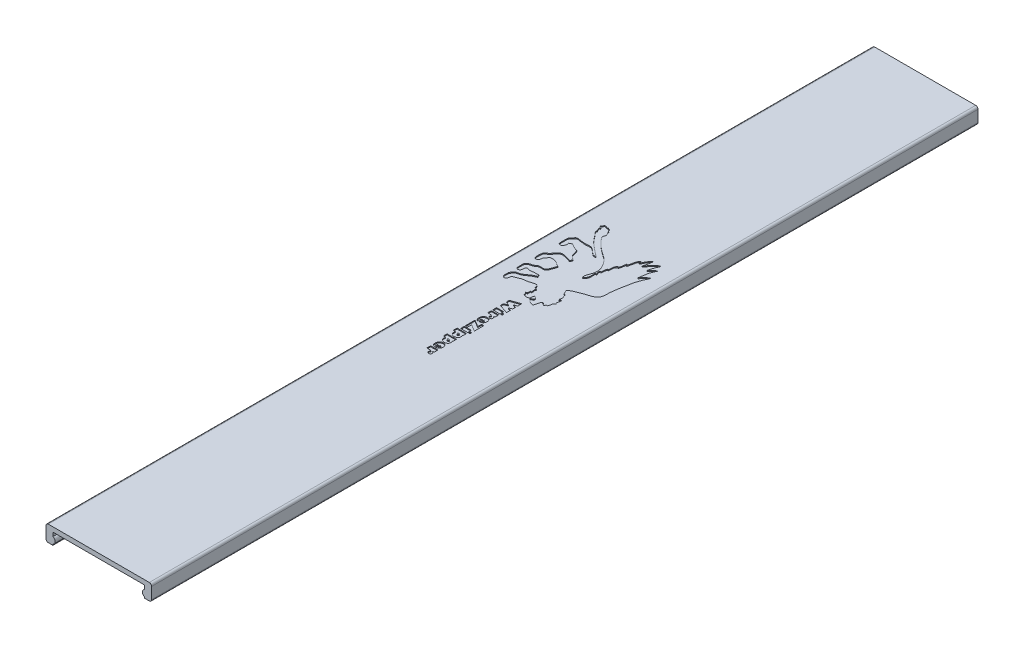
SolidWorks part; units mm, degrees
ref_plane "Front Plane" through (0, 0, 0) normal (0, 0, 1) x (1, 0, 0)
ref_plane "Top Plane" through (0, 0, 0) normal (0, 1, 0) x (1, 0, 0)
ref_plane "Right Plane" through (0, 0, 0) normal (1, 0, 0) x (0, 0, -1)
sketch "Sketch1" plane through (0, 0, 0) normal (0, 0, 1) x (1, 0, 0)
  line L0 (21.5, 0) -> (22.5, 0)
  line L1 (0.5, 0) -> (1.5, 0)
  line L2 (0, 0.5) -> (0, 3)
  line L3 (0.5, 3.5) -> (22.5, 3.5)
  line L4 (23, 0.5) -> (23, 3)
  line L5 (1.5, 2.5) -> (21.5, 2.5)
  line L6 (1.5, 2.5) -> (1.5, 1.637)
  line L8 (21.5, 2.5) -> (21.5, 1.637)
  line L9 (1.5, 0.2228) -> (1.5, 0)
  line L10 (1.25, 0.9299) -> (21.75, 0.9299) construction
  line L11 (21.5, 0.2228) -> (21.5, 0)
  arc A1 (1.5, 0.2228) -> (1.5, 1.637) centre (1.25, 0.9299) ccw
  arc A2 (21.5, 1.637) -> (21.5, 0.2228) centre (21.75, 0.9299) ccw
  arc A3 (23, 3) -> (22.5, 3.5) centre (22.5, 3) ccw
  arc A4 (0.5, 3.5) -> (0, 3) centre (0.5, 3) ccw
  arc A5 (23, 0.5) -> (22.5, 0) centre (22.5, 0.5) cw
  arc A6 (0, 0.5) -> (0.5, 0) centre (0.5, 0.5) ccw
  point P9 (11.5, 2.5)
  point P10 (11.5, 3.5)
  point P11 (0, 1.75)
  point P20 (23, 3.5)
  point P23 (0, 3.5)
  point P28 (0, 0)
  dimension "D6" = 1.5
  dimension "D9" = 0.5
  dimension "D10" = 0.5
  dimension "D1" = 23
  dimension "D2" = 3.5
  dimension "D3" = 1
  dimension "D4" = 1.5
  dimension "D5" = 20
  dimension "D7" = 0.25
  dimension "D8" = 0.25
extrude "Boss-Extrude1" add sketch "Sketch1" along normal blind 180
sketch "Sketch2" plane through (0, 3.5, 0) normal (0, 1, 0) x (1, 0, 0)
  line L4 (19.7713, -68.0162) -> (19.7056, -68.0387)
  line L5 (19.7056, -68.0387) -> (19.6414, -68.0638)
  line L6 (19.6414, -68.0638) -> (19.5786, -68.0912)
  line L7 (19.5786, -68.0912) -> (19.5173, -68.1208)
  line L8 (19.5173, -68.1208) -> (19.4572, -68.1527)
  line L9 (19.4572, -68.1527) -> (19.3985, -68.1865)
  line L10 (19.3985, -68.1865) -> (19.341, -68.2223)
  line L11 (19.341, -68.2223) -> (19.2846, -68.2598)
  line L12 (19.2846, -68.2598) -> (19.2294, -68.2991)
  line L13 (19.2294, -68.2991) -> (19.1752, -68.34)
  line L14 (19.1752, -68.34) -> (19.122, -68.3824)
  line L15 (19.122, -68.3824) -> (19.0697, -68.4261)
  line L16 (19.0697, -68.4261) -> (19.0184, -68.4711)
  line L17 (19.0184, -68.4711) -> (18.918, -68.5644)
  line L18 (18.918, -68.5644) -> (18.7727, -68.711)
  line L19 (18.7727, -68.711) -> (18.2698, -69.2714)
  line L20 (18.2698, -69.2714) -> (18.2812, -69.1529)
  line L21 (18.2812, -69.1529) -> (18.535, -67.5691)
  line L22 (18.535, -67.5691) -> (18.544, -67.5095)
  line L23 (18.544, -67.5095) -> (18.5547, -67.4504)
  line L24 (18.5547, -67.4504) -> (18.567, -67.3918)
  line L25 (18.567, -67.3918) -> (18.5808, -67.3338)
  line L26 (18.5808, -67.3338) -> (18.6125, -67.2189)
  line L27 (18.6125, -67.2189) -> (18.649, -67.1057)
  line L28 (18.649, -67.1057) -> (18.7112, -66.9383)
  line L29 (18.7112, -66.9383) -> (19.0474, -66.172)
  line L30 (19.0474, -66.172) -> (19.1337, -65.9499)
  line L31 (19.1337, -65.9499) -> (19.0766, -65.96)
  line L32 (19.0766, -65.96) -> (19.021, -65.9729)
  line L33 (19.021, -65.9729) -> (18.9668, -65.9885)
  line L34 (18.9668, -65.9885) -> (18.9139, -66.0067)
  line L35 (18.9139, -66.0067) -> (18.8624, -66.0273)
  line L36 (18.8624, -66.0273) -> (18.812, -66.0502)
  line L37 (18.812, -66.0502) -> (18.7628, -66.0753)
  line L38 (18.7628, -66.0753) -> (18.7147, -66.1024)
  line L39 (18.7147, -66.1024) -> (18.6677, -66.1313)
  line L40 (18.6677, -66.1313) -> (18.6216, -66.1621)
  line L41 (18.6216, -66.1621) -> (18.5764, -66.1944)
  line L42 (18.5764, -66.1944) -> (18.5321, -66.2282)
  line L43 (18.5321, -66.2282) -> (18.4458, -66.2997)
  line L44 (18.4458, -66.2997) -> (18.3621, -66.3754)
  line L45 (18.3621, -66.3754) -> (18.2006, -66.5354)
  line L46 (18.2006, -66.5354) -> (17.8477, -66.8963)
  line L47 (17.8477, -66.8963) -> (17.8847, -66.737)
  line L48 (17.8847, -66.737) -> (17.9683, -66.4211)
  line L49 (17.9683, -66.4211) -> (18.0638, -66.1089)
  line L50 (18.0638, -66.1089) -> (18.226, -65.6467)
  line L51 (18.226, -65.6467) -> (18.633, -64.6662)
  line L52 (18.633, -64.6662) -> (18.5994, -64.6698)
  line L53 (18.5994, -64.6698) -> (18.5332, -64.6806)
  line L54 (18.5332, -64.6806) -> (18.4685, -64.6959)
  line L55 (18.4685, -64.6959) -> (18.4051, -64.7155)
  line L56 (18.4051, -64.7155) -> (18.3126, -64.752)
  line L57 (18.3126, -64.752) -> (18.2231, -64.7961)
  line L58 (18.2231, -64.7961) -> (18.0805, -64.8835)
  line L59 (18.0805, -64.8835) -> (17.7942, -65.1134)
  line L60 (17.7942, -65.1134) -> (17.0691, -65.9091)
  line L61 (17.0691, -65.9091) -> (16.8287, -66.2416)
  line L62 (16.8287, -66.2416) -> (16.513, -66.6563)
  line L63 (16.513, -66.6563) -> (16.7942, -65.369)
  line L64 (16.7942, -65.369) -> (16.9419, -64.5963)
  line L65 (16.9419, -64.5963) -> (16.8708, -64.6363)
  line L66 (16.8708, -64.6363) -> (16.8028, -64.6792)
  line L67 (16.8028, -64.6792) -> (16.7378, -64.7251)
  line L68 (16.7378, -64.7251) -> (16.6757, -64.7737)
  line L69 (16.6757, -64.7737) -> (16.6162, -64.8249)
  line L70 (16.6162, -64.8249) -> (16.5593, -64.8785)
  line L71 (16.5593, -64.8785) -> (16.5048, -64.9343)
  line L72 (16.5048, -64.9343) -> (16.4525, -64.9923)
  line L73 (16.4525, -64.9923) -> (16.4023, -65.0522)
  line L74 (16.4023, -65.0522) -> (16.3541, -65.114)
  line L75 (16.3541, -65.114) -> (16.3077, -65.1774)
  line L76 (16.3077, -65.1774) -> (16.263, -65.2423)
  line L77 (16.263, -65.2423) -> (16.2198, -65.3086)
  line L78 (16.2198, -65.3086) -> (16.178, -65.3761)
  line L79 (16.178, -65.3761) -> (16.0979, -65.514)
  line L80 (16.0979, -65.514) -> (15.9845, -65.7262)
  line L81 (15.9845, -65.7262) -> (15.694, -66.2934)
  line L82 (15.694, -66.2934) -> (15.6177, -66.4289)
  line L83 (15.6177, -66.4289) -> (15.549, -65.8484)
  line L84 (15.549, -65.8484) -> (15.5225, -65.8651)
  line L85 (15.5225, -65.8651) -> (15.4723, -65.9013)
  line L86 (15.4723, -65.9013) -> (15.426, -65.9412)
  line L87 (15.426, -65.9412) -> (15.3833, -65.9844)
  line L88 (15.3833, -65.9844) -> (15.3439, -66.0306)
  line L89 (15.3439, -66.0306) -> (15.2905, -66.1046)
  line L90 (15.2905, -66.1046) -> (15.2284, -66.2106)
  line L91 (15.2284, -66.2106) -> (15.0765, -66.58)
  line L92 (15.0765, -66.58) -> (15.0409, -66.6935)
  line L93 (15.0409, -66.6935) -> (14.6863, -68.2584)
  line L94 (14.6863, -68.2584) -> (14.4749, -67.9375)
  line L95 (14.4749, -67.9375) -> (14.4456, -68.1048)
  line L96 (14.4456, -68.1048) -> (14.3106, -68.9476)
  line L97 (14.3106, -68.9476) -> (14.2712, -69.1132)
  line L98 (14.2712, -69.1132) -> (14.24, -69.2224)
  line L99 (14.24, -69.2224) -> (14.2042, -69.3303)
  line L100 (14.2042, -69.3303) -> (14.1631, -69.4368)
  line L101 (14.1631, -69.4368) -> (14.1404, -69.4895)
  line L102 (14.1404, -69.4895) -> (14.1161, -69.5418)
  line L103 (14.1161, -69.5418) -> (13.9814, -69.4095)
  line L104 (13.9814, -69.4095) -> (13.7581, -69.6328)
  line L105 (13.7581, -69.6328) -> (13.6767, -69.7542)
  line L106 (13.6767, -69.7542) -> (13.6425, -69.8308)
  line L107 (13.6425, -69.8308) -> (13.6243, -69.8924)
  line L108 (13.6243, -69.8924) -> (13.6148, -69.9324)
  line L109 (13.6148, -69.9324) -> (13.592, -70.0527)
  line L110 (13.592, -70.0527) -> (13.5689, -70.255)
  line L111 (13.5689, -70.255) -> (13.5297, -71.0705)
  line L112 (13.5297, -71.0705) -> (13.3341, -70.9606)
  line L113 (13.3341, -70.9606) -> (13.3022, -71.0425)
  line L114 (13.3022, -71.0425) -> (13.248, -71.2091)
  line L115 (13.248, -71.2091) -> (13.2062, -71.3788)
  line L116 (13.2062, -71.3788) -> (13.1698, -71.5941)
  line L117 (13.1698, -71.5941) -> (13.1475, -71.8557)
  line L118 (13.1475, -71.8557) -> (13.1495, -72.206)
  line L119 (13.1495, -72.206) -> (12.9637, -72.2453)
  line L120 (12.9637, -72.2453) -> (12.9195, -72.274)
  line L121 (12.9195, -72.274) -> (12.8989, -72.299)
  line L122 (12.8989, -72.299) -> (12.8883, -72.3195)
  line L123 (12.8883, -72.3195) -> (12.8805, -72.3435)
  line L124 (12.8805, -72.3435) -> (12.874, -72.3729)
  line L125 (12.874, -72.3729) -> (12.8656, -72.4318)
  line L126 (12.8656, -72.4318) -> (12.8625, -72.4903)
  line L127 (12.8625, -72.4903) -> (12.8643, -72.5487)
  line L128 (12.8643, -72.5487) -> (12.8705, -72.6068)
  line L129 (12.8705, -72.6068) -> (12.8937, -72.722)
  line L130 (12.8937, -72.722) -> (13.0558, -73.168)
  line L131 (13.0558, -73.168) -> (12.7626, -73.0589)
  line L132 (12.7626, -73.0589) -> (12.7728, -74.2235)
  line L133 (12.7728, -74.2235) -> (12.7694, -74.268)
  line L134 (12.7694, -74.268) -> (12.7642, -74.3119)
  line L135 (12.7642, -74.3119) -> (12.7573, -74.3554)
  line L136 (12.7573, -74.3554) -> (12.7487, -74.3983)
  line L137 (12.7487, -74.3983) -> (12.7384, -74.4406)
  line L138 (12.7384, -74.4406) -> (12.7265, -74.4825)
  line L139 (12.7265, -74.4825) -> (12.7131, -74.5237)
  line L140 (12.7131, -74.5237) -> (12.6982, -74.5644)
  line L141 (12.6982, -74.5644) -> (12.6819, -74.6046)
  line L142 (12.6819, -74.6046) -> (12.6642, -74.6441)
  line L143 (12.6642, -74.6441) -> (12.6248, -74.7214)
  line L144 (12.6248, -74.7214) -> (12.5806, -74.7963)
  line L145 (12.5806, -74.7963) -> (12.5319, -74.8686)
  line L146 (12.5319, -74.8686) -> (12.4791, -74.9384)
  line L147 (12.4791, -74.9384) -> (12.4226, -75.0055)
  line L148 (12.4226, -75.0055) -> (12.332, -75.1011)
  line L149 (12.332, -75.1011) -> (12.2356, -75.1902)
  line L150 (12.2356, -75.1902) -> (12.1347, -75.2728)
  line L151 (12.1347, -75.2728) -> (12.0463, -74.8208)
  line L152 (12.0463, -74.8208) -> (12.0572, -74.7514)
  line L153 (12.0572, -74.7514) -> (12.0701, -74.6825)
  line L154 (12.0701, -74.6825) -> (12.0846, -74.6141)
  line L155 (12.0846, -74.6141) -> (12.1008, -74.546)
  line L156 (12.1008, -74.546) -> (12.1374, -74.4111)
  line L157 (12.1374, -74.4111) -> (12.2004, -74.2109)
  line L158 (12.2004, -74.2109) -> (12.4552, -73.4833)
  line L159 (12.4552, -73.4833) -> (12.4951, -73.3494)
  line L160 (12.4951, -73.3494) -> (12.5302, -73.2142)
  line L161 (12.5302, -73.2142) -> (12.5455, -73.1461)
  line L162 (12.5455, -73.1461) -> (12.5591, -73.0775)
  line L163 (12.5591, -73.0775) -> (12.5709, -73.0084)
  line L164 (12.5709, -73.0084) -> (12.5807, -72.9388)
  line L165 (12.5807, -72.9388) -> (12.5884, -72.8687)
  line L166 (12.5884, -72.8687) -> (12.5946, -72.8106)
  line L167 (12.5946, -72.8106) -> (12.6038, -72.6941)
  line L168 (12.6038, -72.6941) -> (12.6085, -72.5773)
  line L169 (12.6085, -72.5773) -> (12.6087, -72.4603)
  line L170 (12.6087, -72.4603) -> (12.6042, -72.3433)
  line L171 (12.6042, -72.3433) -> (12.5951, -72.2267)
  line L172 (12.5951, -72.2267) -> (12.5813, -72.1106)
  line L173 (12.5813, -72.1106) -> (12.5626, -71.9952)
  line L174 (12.5626, -71.9952) -> (12.5392, -71.8808)
  line L175 (12.5392, -71.8808) -> (12.5108, -71.7675)
  line L176 (12.5108, -71.7675) -> (12.4775, -71.6556)
  line L177 (12.4775, -71.6556) -> (12.4392, -71.5453)
  line L178 (12.4392, -71.5453) -> (12.3958, -71.4368)
  line L179 (12.3958, -71.4368) -> (12.3473, -71.3303)
  line L180 (12.3473, -71.3303) -> (12.2936, -71.2261)
  line L181 (12.2936, -71.2261) -> (12.1536, -70.9726)
  line L182 (12.1536, -70.9726) -> (12.0556, -70.8056)
  line L183 (12.0556, -70.8056) -> (11.9537, -70.6406)
  line L184 (11.9537, -70.6406) -> (11.8476, -70.4782)
  line L185 (11.8476, -70.4782) -> (11.7372, -70.3187)
  line L186 (11.7372, -70.3187) -> (11.6223, -70.1625)
  line L187 (11.6223, -70.1625) -> (11.5631, -70.0859)
  line L188 (11.5631, -70.0859) -> (11.5027, -70.0102)
  line L189 (11.5027, -70.0102) -> (11.441, -69.9356)
  line L190 (11.441, -69.9356) -> (11.3782, -69.8621)
  line L191 (11.3782, -69.8621) -> (11.3141, -69.7897)
  line L192 (11.3141, -69.7897) -> (11.2486, -69.7186)
  line L193 (11.2486, -69.7186) -> (11.1819, -69.6487)
  line L194 (11.1819, -69.6487) -> (11.1139, -69.5802)
  line L195 (11.1139, -69.5802) -> (11.0445, -69.513)
  line L196 (11.0445, -69.513) -> (10.9737, -69.4473)
  line L197 (10.9737, -69.4473) -> (10.9015, -69.383)
  line L198 (10.9015, -69.383) -> (10.8279, -69.3203)
  line L199 (10.8279, -69.3203) -> (10.7528, -69.2592)
  line L200 (10.7528, -69.2592) -> (10.6763, -69.1997)
  line L201 (10.6763, -69.1997) -> (10.5982, -69.1419)
  line L202 (10.5982, -69.1419) -> (10.5187, -69.0859)
  line L203 (10.5187, -69.0859) -> (9.4452, -68.33)
  line L204 (9.4452, -68.33) -> (9.3773, -68.2867)
  line L205 (9.3773, -68.2867) -> (8.53, -67.6115)
  line L206 (8.53, -67.6115) -> (8.3361, -67.4547)
  line L207 (8.3361, -67.4547) -> (8.1475, -67.2919)
  line L208 (8.1475, -67.2919) -> (7.9041, -67.0658)
  line L209 (7.9041, -67.0658) -> (7.6696, -66.8305)
  line L210 (7.6696, -66.8305) -> (7.4436, -66.5867)
  line L211 (7.4436, -66.5867) -> (7.173, -66.2715)
  line L212 (7.173, -66.2715) -> (6.8648, -65.88)
  line L213 (6.8648, -65.88) -> (6.7097, -65.6569)
  line L214 (6.7097, -65.6569) -> (6.6566, -65.5438)
  line L215 (6.6566, -65.5438) -> (6.6407, -65.4743)
  line L216 (6.6407, -65.4743) -> (6.638, -65.4193)
  line L217 (6.638, -65.4193) -> (6.637, -65.3934)
  line L218 (6.637, -65.3934) -> (6.6379, -65.3678)
  line L219 (6.6379, -65.3678) -> (6.6403, -65.3423)
  line L220 (6.6403, -65.3423) -> (6.6494, -65.2922)
  line L221 (6.6494, -65.2922) -> (6.6631, -65.2427)
  line L222 (6.6631, -65.2427) -> (6.7675, -64.9759)
  line L223 (6.7675, -64.9759) -> (6.7877, -64.9024)
  line L224 (6.7877, -64.9024) -> (6.7953, -64.8526)
  line L225 (6.7953, -64.8526) -> (6.7968, -64.8275)
  line L226 (6.7968, -64.8275) -> (6.7967, -64.8021)
  line L227 (6.7967, -64.8021) -> (6.7947, -64.7765)
  line L228 (6.7947, -64.7765) -> (6.7907, -64.7506)
  line L229 (6.7907, -64.7506) -> (6.7846, -64.7245)
  line L230 (6.7846, -64.7245) -> (6.7763, -64.698)
  line L231 (6.7763, -64.698) -> (6.4789, -63.8339)
  line L232 (6.4789, -63.8339) -> (6.3162, -63.8719)
  line L233 (6.3162, -63.8719) -> (6.0814, -63.2667)
  line L234 (6.0814, -63.2667) -> (5.9437, -63.4423)
  line L235 (5.9437, -63.4423) -> (5.6179, -63.0803)
  line L236 (5.6179, -63.0803) -> (5.4993, -63.2471)
  line L237 (5.4993, -63.2471) -> (5.4182, -63.2127)
  line L238 (5.4182, -63.2127) -> (5.0832, -63.1098)
  line L239 (5.0832, -63.1098) -> (4.852, -63.0789)
  line L240 (4.852, -63.0789) -> (4.6755, -63.0793)
  line L241 (4.6755, -63.0793) -> (4.6672, -63.3323)
  line L242 (4.6672, -63.3323) -> (4.3029, -63.6837)
  line L243 (4.3029, -63.6837) -> (4.4364, -63.7454)
  line L244 (4.4364, -63.7454) -> (4.6822, -63.862)
  line L245 (4.6822, -63.862) -> (4.7406, -63.904)
  line L246 (4.7406, -63.904) -> (4.7757, -63.9362)
  line L247 (4.7757, -63.9362) -> (4.8071, -63.9724)
  line L248 (4.8071, -63.9724) -> (4.8213, -63.9922)
  line L249 (4.8213, -63.9922) -> (4.8345, -64.0131)
  line L250 (4.8345, -64.0131) -> (4.8464, -64.0354)
  line L251 (4.8464, -64.0354) -> (4.8571, -64.059)
  line L252 (4.8571, -64.059) -> (4.8666, -64.0839)
  line L253 (4.8666, -64.0839) -> (4.6194, -64.1381)
  line L254 (4.6194, -64.1381) -> (4.6364, -64.2183)
  line L255 (4.6364, -64.2183) -> (4.6966, -64.3979)
  line L256 (4.6966, -64.3979) -> (4.9547, -64.8424)
  line L257 (4.9547, -64.8424) -> (4.8825, -65.0571)
  line L258 (4.8825, -65.0571) -> (4.8809, -65.1758)
  line L259 (4.8809, -65.1758) -> (4.9013, -65.2205)
  line L260 (4.9013, -65.2205) -> (4.9626, -65.3253)
  line L261 (4.9626, -65.3253) -> (5.3289, -65.7142)
  line L262 (5.3289, -65.7142) -> (5.3543, -65.7372)
  line L263 (5.3543, -65.7372) -> (5.4262, -65.8098)
  line L264 (5.4262, -65.8098) -> (5.5342, -65.9403)
  line L265 (5.5342, -65.9403) -> (5.9242, -66.4974)
  line L266 (5.9242, -66.4974) -> (5.9941, -66.5912)
  line L267 (5.9941, -66.5912) -> (6.0655, -66.6837)
  line L268 (6.0655, -66.6837) -> (6.1382, -66.7749)
  line L269 (6.1382, -66.7749) -> (6.2123, -66.8649)
  line L270 (6.2123, -66.8649) -> (6.2877, -66.9537)
  line L271 (6.2877, -66.9537) -> (6.3643, -67.0414)
  line L272 (6.3643, -67.0414) -> (6.4422, -67.128)
  line L273 (6.4422, -67.128) -> (6.5212, -67.2135)
  line L274 (6.5212, -67.2135) -> (6.6012, -67.2979)
  line L275 (6.6012, -67.2979) -> (6.7645, -67.4639)
  line L276 (6.7645, -67.4639) -> (6.9315, -67.6263)
  line L277 (6.9315, -67.6263) -> (7.102, -67.7852)
  line L278 (7.102, -67.7852) -> (7.2754, -67.9411)
  line L279 (7.2754, -67.9411) -> (7.5403, -68.1699)
  line L280 (7.5403, -68.1699) -> (8.3562, -68.8291)
  line L281 (8.3562, -68.8291) -> (8.3997, -68.8707)
  line L282 (8.3997, -68.8707) -> (8.4887, -68.9512)
  line L283 (8.4887, -68.9512) -> (8.6269, -69.0657)
  line L284 (8.6269, -69.0657) -> (8.9149, -69.2793)
  line L285 (8.9149, -69.2793) -> (9.5957, -69.7675)
  line L286 (9.5957, -69.7675) -> (9.7335, -69.883)
  line L287 (9.7335, -69.883) -> (9.2384, -69.9121)
  line L288 (9.2384, -69.9121) -> (9.1226, -69.8981)
  line L289 (9.1226, -69.8981) -> (9.0543, -69.8802)
  line L290 (9.0543, -69.8802) -> (8.9059, -69.7676)
  line L291 (8.9059, -69.7676) -> (7.9015, -68.9336)
  line L292 (7.9015, -68.9336) -> (7.6513, -68.7497)
  line L293 (7.6513, -68.7497) -> (7.6022, -68.7188)
  line L294 (7.6022, -68.7188) -> (7.5523, -68.6913)
  line L295 (7.5523, -68.6913) -> (7.5017, -68.667)
  line L296 (7.5017, -68.667) -> (7.4505, -68.6458)
  line L297 (7.4505, -68.6458) -> (7.3986, -68.6275)
  line L298 (7.3986, -68.6275) -> (7.3462, -68.612)
  line L299 (7.3462, -68.612) -> (7.2932, -68.599)
  line L300 (7.2932, -68.599) -> (7.2397, -68.5885)
  line L301 (7.2397, -68.5885) -> (7.1858, -68.5802)
  line L302 (7.1858, -68.5802) -> (7.1315, -68.5739)
  line L303 (7.1315, -68.5739) -> (7.0768, -68.5696)
  line L304 (7.0768, -68.5696) -> (7.0217, -68.5671)
  line L305 (7.0217, -68.5671) -> (6.9108, -68.5665)
  line L306 (6.9108, -68.5665) -> (6.7431, -68.5748)
  line L307 (6.7431, -68.5748) -> (6.1852, -68.6265)
  line L308 (6.1852, -68.6265) -> (6.0763, -68.6314)
  line L309 (6.0763, -68.6314) -> (4.992, -68.5326)
  line L310 (4.992, -68.5326) -> (4.8611, -68.5147)
  line L311 (4.8611, -68.5147) -> (4.3666, -68.4393)
  line L312 (4.3666, -68.4393) -> (4.2677, -68.4378)
  line L313 (4.2677, -68.4378) -> (4.2019, -68.4418)
  line L314 (4.2019, -68.4418) -> (4.1362, -68.4506)
  line L315 (4.1362, -68.4506) -> (4.0706, -68.4648)
  line L316 (4.0706, -68.4648) -> (4.0379, -68.4741)
  line L317 (4.0379, -68.4741) -> (4.014, -68.4828)
  line L318 (4.014, -68.4828) -> (3.9912, -68.4926)
  line L319 (3.9912, -68.4926) -> (3.9694, -68.5037)
  line L320 (3.9694, -68.5037) -> (3.9287, -68.5289)
  line L321 (3.9287, -68.5289) -> (3.8914, -68.5581)
  line L322 (3.8914, -68.5581) -> (3.857, -68.5905)
  line L323 (3.857, -68.5905) -> (3.7809, -68.6828)
  line L324 (3.7809, -68.6828) -> (3.575, -68.9832)
  line L325 (3.575, -68.9832) -> (3.5102, -69.0651)
  line L326 (3.5102, -69.0651) -> (3.2556, -69.3376)
  line L327 (3.2556, -69.3376) -> (3.2114, -69.4017)
  line L328 (3.2114, -69.4017) -> (3.1867, -69.4471)
  line L329 (3.1867, -69.4471) -> (3.1668, -69.4951)
  line L330 (3.1668, -69.4951) -> (3.1589, -69.5201)
  line L331 (3.1589, -69.5201) -> (3.1524, -69.5459)
  line L332 (3.1524, -69.5459) -> (3.1474, -69.5726)
  line L333 (3.1474, -69.5726) -> (3.144, -69.6001)
  line L334 (3.144, -69.6001) -> (3.14, -69.6565)
  line L335 (3.14, -69.6565) -> (3.1406, -71.2386)
  line L336 (3.1406, -71.2386) -> (3.1441, -71.2775)
  line L337 (3.1441, -71.2775) -> (3.1837, -71.4053)
  line L338 (3.1837, -71.4053) -> (3.2293, -71.4697)
  line L339 (3.2293, -71.4697) -> (3.2692, -71.5026)
  line L340 (3.2692, -71.5026) -> (3.3044, -71.5205)
  line L341 (3.3044, -71.5205) -> (3.3442, -71.5313)
  line L342 (3.3442, -71.5313) -> (3.6184, -71.552)
  line L343 (3.6184, -71.552) -> (3.7097, -71.5433)
  line L344 (3.7097, -71.5433) -> (3.7753, -71.5281)
  line L345 (3.7753, -71.5281) -> (3.8171, -71.513)
  line L346 (3.8171, -71.513) -> (3.857, -71.4934)
  line L347 (3.857, -71.4934) -> (3.8945, -71.4689)
  line L348 (3.8945, -71.4689) -> (3.9123, -71.4547)
  line L349 (3.9123, -71.4547) -> (3.9294, -71.4391)
  line L350 (3.9294, -71.4391) -> (3.9457, -71.422)
  line L351 (3.9457, -71.422) -> (3.9613, -71.4035)
  line L352 (3.9613, -71.4035) -> (3.9894, -71.3736)
  line L353 (3.9894, -71.3736) -> (4.0159, -71.3428)
  line L354 (4.0159, -71.3428) -> (4.0409, -71.3111)
  line L355 (4.0409, -71.3111) -> (4.0643, -71.2784)
  line L356 (4.0643, -71.2784) -> (4.0862, -71.2449)
  line L357 (4.0862, -71.2449) -> (4.1066, -71.2106)
  line L358 (4.1066, -71.2106) -> (4.1255, -71.1756)
  line L359 (4.1255, -71.1756) -> (4.1429, -71.1399)
  line L360 (4.1429, -71.1399) -> (4.1588, -71.1035)
  line L361 (4.1588, -71.1035) -> (4.1732, -71.0666)
  line L362 (4.1732, -71.0666) -> (4.1862, -71.0291)
  line L363 (4.1862, -71.0291) -> (4.1977, -70.9912)
  line L364 (4.1977, -70.9912) -> (4.2078, -70.9528)
  line L365 (4.2078, -70.9528) -> (4.2164, -70.914)
  line L366 (4.2164, -70.914) -> (4.2236, -70.8749)
  line L367 (4.2236, -70.8749) -> (4.2338, -70.7958)
  line L368 (4.2338, -70.7958) -> (4.2385, -70.7161)
  line L369 (4.2385, -70.7161) -> (4.2376, -70.636)
  line L370 (4.2376, -70.636) -> (4.2314, -70.556)
  line L371 (4.2314, -70.556) -> (4.2198, -70.4765)
  line L372 (4.2198, -70.4765) -> (4.203, -70.3979)
  line L373 (4.203, -70.3979) -> (4.181, -70.3206)
  line L374 (4.181, -70.3206) -> (4.7901, -70.0484)
  line L375 (4.7901, -70.0484) -> (5.2245, -70.3466)
  line L376 (5.2245, -70.3466) -> (5.4751, -70.4867)
  line L377 (5.4751, -70.4867) -> (5.6484, -70.5673)
  line L378 (5.6484, -70.5673) -> (5.7819, -70.6197)
  line L379 (5.7819, -70.6197) -> (5.9186, -70.6643)
  line L380 (5.9186, -70.6643) -> (6.0116, -70.6894)
  line L381 (6.0116, -70.6894) -> (6.4412, -70.8042)
  line L382 (6.4412, -70.8042) -> (6.6803, -71.4735)
  line L383 (6.6803, -71.4735) -> (6.7004, -71.5284)
  line L384 (6.7004, -71.5284) -> (6.7442, -71.699)
  line L385 (6.7442, -71.699) -> (6.8306, -72.1014)
  line L386 (6.8306, -72.1014) -> (6.8618, -72.1829)
  line L387 (6.8618, -72.1829) -> (6.8877, -72.2354)
  line L388 (6.8877, -72.2354) -> (6.9183, -72.2862)
  line L389 (6.9183, -72.2862) -> (6.9701, -72.3445)
  line L390 (6.9701, -72.3445) -> (7.1086, -72.4804)
  line L391 (7.1086, -72.4804) -> (7.7939, -72.9919)
  line L392 (7.7939, -72.9919) -> (7.7351, -73.1517)
  line L393 (7.7351, -73.1517) -> (7.6452, -73.3187)
  line L394 (7.6452, -73.3187) -> (7.5925, -73.3834)
  line L395 (7.5925, -73.3834) -> (7.5465, -73.4263)
  line L396 (7.5465, -73.4263) -> (7.4942, -73.4637)
  line L397 (7.4942, -73.4637) -> (7.4555, -73.4852)
  line L398 (7.4555, -73.4852) -> (6.9853, -73.3177)
  line L399 (6.9853, -73.3177) -> (6.4139, -73.1402)
  line L400 (6.4139, -73.1402) -> (6.2188, -73.0984)
  line L401 (6.2188, -73.0984) -> (6.0703, -73.0755)
  line L402 (6.0703, -73.0755) -> (6.002, -73.0661)
  line L403 (6.002, -73.0661) -> (5.6117, -73.0217)
  line L404 (5.6117, -73.0217) -> (5.5053, -73.0221)
  line L405 (5.5053, -73.0221) -> (5.4354, -73.0278)
  line L406 (5.4354, -73.0278) -> (5.3668, -73.0388)
  line L407 (5.3668, -73.0388) -> (5.3331, -73.0464)
  line L408 (5.3331, -73.0464) -> (5.2997, -73.0557)
  line L409 (5.2997, -73.0557) -> (5.2669, -73.0666)
  line L410 (5.2669, -73.0666) -> (5.2345, -73.0793)
  line L411 (5.2345, -73.0793) -> (5.2027, -73.0938)
  line L412 (5.2027, -73.0938) -> (5.1715, -73.1103)
  line L413 (5.1715, -73.1103) -> (5.1409, -73.1288)
  line L414 (5.1409, -73.1288) -> (5.111, -73.1495)
  line L415 (5.111, -73.1495) -> (5.0818, -73.1724)
  line L416 (5.0818, -73.1724) -> (5.0388, -73.2082)
  line L417 (5.0388, -73.2082) -> (4.9143, -73.3196)
  line L418 (4.9143, -73.3196) -> (4.7183, -73.5171)
  line L419 (4.7183, -73.5171) -> (3.986, -74.3579)
  line L420 (3.986, -74.3579) -> (3.4335, -74.7985)
  line L421 (3.4335, -74.7985) -> (3.2432, -74.9884)
  line L422 (3.2432, -74.9884) -> (3.2042, -75.1321)
  line L423 (3.2042, -75.1321) -> (3.1326, -75.8459)
  line L424 (3.1326, -75.8459) -> (3.1308, -76.2528)
  line L425 (3.1308, -76.2528) -> (3.1487, -76.422)
  line L426 (3.1487, -76.422) -> (3.1689, -76.5211)
  line L427 (3.1689, -76.5211) -> (3.1872, -76.5856)
  line L428 (3.1872, -76.5856) -> (3.2098, -76.6487)
  line L429 (3.2098, -76.6487) -> (3.2373, -76.71)
  line L430 (3.2373, -76.71) -> (3.2699, -76.7694)
  line L431 (3.2699, -76.7694) -> (3.2883, -76.7983)
  line L432 (3.2883, -76.7983) -> (3.3292, -76.819)
  line L433 (3.3292, -76.819) -> (3.3932, -76.8429)
  line L434 (3.3932, -76.8429) -> (3.4598, -76.8586)
  line L435 (3.4598, -76.8586) -> (3.5512, -76.8679)
  line L436 (3.5512, -76.8679) -> (3.644, -76.8649)
  line L437 (3.644, -76.8649) -> (3.7814, -76.8404)
  line L438 (3.7814, -76.8404) -> (3.9314, -76.7866)
  line L439 (3.9314, -76.7866) -> (3.9502, -76.7698)
  line L440 (3.9502, -76.7698) -> (3.9676, -76.7523)
  line L441 (3.9676, -76.7523) -> (3.9837, -76.7339)
  line L442 (3.9837, -76.7339) -> (4.012, -76.6951)
  line L443 (4.012, -76.6951) -> (4.0358, -76.6537)
  line L444 (4.0358, -76.6537) -> (4.0557, -76.6102)
  line L445 (4.0557, -76.6102) -> (4.0855, -76.5179)
  line L446 (4.0855, -76.5179) -> (4.1545, -76.1303)
  line L447 (4.1545, -76.1303) -> (4.1578, -76.0999)
  line L448 (4.1578, -76.0999) -> (4.1626, -76.0703)
  line L449 (4.1626, -76.0703) -> (4.169, -76.0415)
  line L450 (4.169, -76.0415) -> (4.1769, -76.0135)
  line L451 (4.1769, -76.0135) -> (4.1968, -75.9596)
  line L452 (4.1968, -75.9596) -> (4.2214, -75.9082)
  line L453 (4.2214, -75.9082) -> (4.2658, -75.8349)
  line L454 (4.2658, -75.8349) -> (4.4881, -75.5651)
  line L455 (4.4881, -75.5651) -> (4.5925, -75.4268)
  line L456 (4.5925, -75.4268) -> (4.7686, -75.1769)
  line L457 (4.7686, -75.1769) -> (4.8234, -75.1263)
  line L458 (4.8234, -75.1263) -> (4.8698, -75.0957)
  line L459 (4.8698, -75.0957) -> (4.9038, -75.0796)
  line L460 (4.9038, -75.0796) -> (4.9405, -75.0674)
  line L461 (4.9405, -75.0674) -> (4.9801, -75.0596)
  line L462 (4.9801, -75.0596) -> (5.022, -75.0473)
  line L463 (5.022, -75.0473) -> (5.0638, -75.037)
  line L464 (5.0638, -75.037) -> (5.1057, -75.0287)
  line L465 (5.1057, -75.0287) -> (5.1475, -75.0223)
  line L466 (5.1475, -75.0223) -> (5.1893, -75.0177)
  line L467 (5.1893, -75.0177) -> (5.2311, -75.0147)
  line L468 (5.2311, -75.0147) -> (5.2729, -75.0134)
  line L469 (5.2729, -75.0134) -> (5.3147, -75.0136)
  line L470 (5.3147, -75.0136) -> (5.3982, -75.018)
  line L471 (5.3982, -75.018) -> (5.4815, -75.0273)
  line L472 (5.4815, -75.0273) -> (5.6062, -75.0489)
  line L473 (5.6062, -75.0489) -> (6.1798, -75.2004)
  line L474 (6.1798, -75.2004) -> (6.2396, -75.2191)
  line L475 (6.2396, -75.2191) -> (6.297, -75.2424)
  line L476 (6.297, -75.2424) -> (6.379, -75.2844)
  line L477 (6.379, -75.2844) -> (6.5333, -75.3862)
  line L478 (6.5333, -75.3862) -> (6.8623, -75.6178)
  line L479 (6.8623, -75.6178) -> (6.945, -75.6597)
  line L480 (6.945, -75.6597) -> (7.3529, -75.8473)
  line L481 (7.3529, -75.8473) -> (7.3353, -75.9277)
  line L482 (7.3353, -75.9277) -> (7.2542, -76.2027)
  line L483 (7.2542, -76.2027) -> (6.9853, -76.977)
  line L484 (6.9853, -76.977) -> (6.9218, -77.1748)
  line L485 (6.9218, -77.1748) -> (6.8417, -77.3713)
  line L486 (6.8417, -77.3713) -> (6.7927, -77.4646)
  line L487 (6.7927, -77.4646) -> (6.7559, -77.5237)
  line L488 (6.7559, -77.5237) -> (6.7156, -77.5798)
  line L489 (6.7156, -77.5798) -> (6.6712, -77.6323)
  line L490 (6.6712, -77.6323) -> (6.6474, -77.657)
  line L491 (6.6474, -77.657) -> (6.6225, -77.6807)
  line L492 (6.6225, -77.6807) -> (6.5965, -77.7032)
  line L493 (6.5965, -77.7032) -> (6.5693, -77.7244)
  line L494 (6.5693, -77.7244) -> (6.5408, -77.7444)
  line L495 (6.5408, -77.7444) -> (6.5111, -77.7629)
  line L496 (6.5111, -77.7629) -> (6.48, -77.7801)
  line L497 (6.48, -77.7801) -> (6.4476, -77.7958)
  line L498 (6.4476, -77.7958) -> (6.4056, -77.8087)
  line L499 (6.4056, -77.8087) -> (6.3634, -77.8195)
  line L500 (6.3634, -77.8195) -> (6.3211, -77.8286)
  line L501 (6.3211, -77.8286) -> (6.2785, -77.8359)
  line L502 (6.2785, -77.8359) -> (6.2358, -77.8416)
  line L503 (6.2358, -77.8416) -> (6.15, -77.849)
  line L504 (6.15, -77.849) -> (6.0204, -77.8517)
  line L505 (6.0204, -77.8517) -> (5.5419, -77.8342)
  line L506 (5.5419, -77.8342) -> (5.4122, -77.8386)
  line L507 (5.4122, -77.8386) -> (5.3262, -77.8475)
  line L508 (5.3262, -77.8475) -> (5.2834, -77.8541)
  line L509 (5.2834, -77.8541) -> (5.2408, -77.8624)
  line L510 (5.2408, -77.8624) -> (5.1984, -77.8725)
  line L511 (5.1984, -77.8725) -> (5.1429, -77.8929)
  line L512 (5.1429, -77.8929) -> (5.0372, -77.9432)
  line L513 (5.0372, -77.9432) -> (4.5955, -78.2327)
  line L514 (4.5955, -78.2327) -> (4.4658, -78.3013)
  line L515 (4.4658, -78.3013) -> (4.4141, -78.3286)
  line L516 (4.4141, -78.3286) -> (4.3608, -78.3512)
  line L517 (4.3608, -78.3512) -> (4.2508, -78.3859)
  line L518 (4.2508, -78.3859) -> (3.8549, -78.4745)
  line L519 (3.8549, -78.4745) -> (3.7737, -78.504)
  line L520 (3.7737, -78.504) -> (3.7213, -78.5287)
  line L521 (3.7213, -78.5287) -> (3.6706, -78.5583)
  line L522 (3.6706, -78.5583) -> (3.6162, -78.5953)
  line L523 (3.6162, -78.5953) -> (3.2174, -79.0006)
  line L524 (3.2174, -79.0006) -> (3.1932, -79.0363)
  line L525 (3.1932, -79.0363) -> (3.1737, -79.0734)
  line L526 (3.1737, -79.0734) -> (3.1523, -79.1314)
  line L527 (3.1523, -79.1314) -> (3.1358, -79.2122)
  line L528 (3.1358, -79.2122) -> (3.1303, -79.5906)
  line L529 (3.1303, -79.5906) -> (3.1317, -79.6254)
  line L530 (3.1317, -79.6254) -> (3.1352, -80.3612)
  line L531 (3.1352, -80.3612) -> (3.1532, -80.4995)
  line L532 (3.1532, -80.4995) -> (3.1755, -80.6021)
  line L533 (3.1755, -80.6021) -> (3.1949, -80.6327)
  line L534 (3.1949, -80.6327) -> (3.2166, -80.6607)
  line L535 (3.2166, -80.6607) -> (3.2403, -80.6861)
  line L536 (3.2403, -80.6861) -> (3.2659, -80.7089)
  line L537 (3.2659, -80.7089) -> (3.2932, -80.7292)
  line L538 (3.2932, -80.7292) -> (3.322, -80.747)
  line L539 (3.322, -80.747) -> (3.3522, -80.7624)
  line L540 (3.3522, -80.7624) -> (3.3836, -80.7752)
  line L541 (3.3836, -80.7752) -> (3.416, -80.7857)
  line L542 (3.416, -80.7857) -> (3.4492, -80.7938)
  line L543 (3.4492, -80.7938) -> (3.4831, -80.7995)
  line L544 (3.4831, -80.7995) -> (3.5175, -80.8029)
  line L545 (3.5175, -80.8029) -> (3.5521, -80.8041)
  line L546 (3.5521, -80.8041) -> (3.587, -80.8029)
  line L547 (3.587, -80.8029) -> (3.6217, -80.7995)
  line L548 (3.6217, -80.7995) -> (3.6563, -80.7939)
  line L549 (3.6563, -80.7939) -> (3.6905, -80.7862)
  line L550 (3.6905, -80.7862) -> (3.7241, -80.7762)
  line L551 (3.7241, -80.7762) -> (3.757, -80.7642)
  line L552 (3.757, -80.7642) -> (3.789, -80.7501)
  line L553 (3.789, -80.7501) -> (3.8199, -80.7339)
  line L554 (3.8199, -80.7339) -> (3.8495, -80.7157)
  line L555 (3.8495, -80.7157) -> (3.8777, -80.6955)
  line L556 (3.8777, -80.6955) -> (3.9043, -80.6733)
  line L557 (3.9043, -80.6733) -> (3.9291, -80.6492)
  line L558 (3.9291, -80.6492) -> (3.9519, -80.6232)
  line L559 (3.9519, -80.6232) -> (3.9726, -80.5953)
  line L560 (3.9726, -80.5953) -> (3.991, -80.5656)
  line L561 (3.991, -80.5656) -> (4.0069, -80.534)
  line L562 (4.0069, -80.534) -> (4.0267, -80.4685)
  line L563 (4.0267, -80.4685) -> (4.042, -80.4016)
  line L564 (4.042, -80.4016) -> (4.0936, -79.9875)
  line L565 (4.0936, -79.9875) -> (4.1181, -79.852)
  line L566 (4.1181, -79.852) -> (4.136, -79.7861)
  line L567 (4.136, -79.7861) -> (4.1589, -79.7219)
  line L568 (4.1589, -79.7219) -> (4.1725, -79.6905)
  line L569 (4.1725, -79.6905) -> (4.1877, -79.6596)
  line L570 (4.1877, -79.6596) -> (4.2046, -79.6293)
  line L571 (4.2046, -79.6293) -> (4.2234, -79.5996)
  line L572 (4.2234, -79.5996) -> (4.2441, -79.5705)
  line L573 (4.2441, -79.5705) -> (4.2943, -79.56)
  line L574 (4.2943, -79.56) -> (4.3945, -79.5495)
  line L575 (4.3945, -79.5495) -> (4.519, -79.5532)
  line L576 (4.519, -79.5532) -> (4.957, -79.6603)
  line L577 (4.957, -79.6603) -> (4.9931, -79.6704)
  line L578 (4.9931, -79.6704) -> (5.0293, -79.6788)
  line L579 (5.0293, -79.6788) -> (5.0656, -79.6855)
  line L580 (5.0656, -79.6855) -> (5.1018, -79.6907)
  line L581 (5.1018, -79.6907) -> (5.1381, -79.6943)
  line L582 (5.1381, -79.6943) -> (5.2106, -79.6976)
  line L583 (5.2106, -79.6976) -> (5.2833, -79.6962)
  line L584 (5.2833, -79.6962) -> (5.3923, -79.6872)
  line L585 (5.3923, -79.6872) -> (5.9018, -79.6117)
  line L586 (5.9018, -79.6117) -> (6.0109, -79.6057)
  line L587 (6.0109, -79.6057) -> (6.9107, -79.5831)
  line L588 (6.9107, -79.5831) -> (7.08, -79.9797)
  line L589 (7.08, -79.9797) -> (6.9606, -80.0183)
  line L590 (6.9606, -80.0183) -> (6.8433, -80.0615)
  line L591 (6.8433, -80.0615) -> (6.7277, -80.1089)
  line L592 (6.7277, -80.1089) -> (6.5577, -80.187)
  line L593 (6.5577, -80.187) -> (6.3912, -80.2727)
  line L594 (6.3912, -80.2727) -> (6.1741, -80.3968)
  line L595 (6.1741, -80.3968) -> (5.4975, -80.8472)
  line L596 (5.4975, -80.8472) -> (5.0502, -81.1631)
  line L597 (5.0502, -81.1631) -> (4.8455, -81.2766)
  line L598 (4.8455, -81.2766) -> (4.7027, -81.3392)
  line L599 (4.7027, -81.3392) -> (4.5918, -81.3776)
  line L600 (4.5918, -81.3776) -> (4.5159, -81.3986)
  line L601 (4.5159, -81.3986) -> (3.9625, -81.5099)
  line L602 (3.9625, -81.5099) -> (3.8363, -81.554)
  line L603 (3.8363, -81.554) -> (3.7636, -81.5898)
  line L604 (3.7636, -81.5898) -> (3.4218, -82.0245)
  line L605 (3.4218, -82.0245) -> (3.2301, -82.263)
  line L606 (3.2301, -82.263) -> (3.1896, -82.3412)
  line L607 (3.1896, -82.3412) -> (3.1742, -82.3919)
  line L608 (3.1742, -82.3919) -> (3.1686, -82.4276)
  line L609 (3.1686, -82.4276) -> (3.1671, -82.465)
  line L610 (3.1671, -82.465) -> (3.1691, -83.3694)
  line L611 (3.1691, -83.3694) -> (3.1712, -83.4048)
  line L612 (3.1712, -83.4048) -> (3.1763, -83.4397)
  line L613 (3.1763, -83.4397) -> (3.1842, -83.4741)
  line L614 (3.1842, -83.4741) -> (3.1949, -83.5078)
  line L615 (3.1949, -83.5078) -> (3.2082, -83.5406)
  line L616 (3.2082, -83.5406) -> (3.224, -83.5725)
  line L617 (3.224, -83.5725) -> (3.242, -83.6033)
  line L618 (3.242, -83.6033) -> (3.2621, -83.6329)
  line L619 (3.2621, -83.6329) -> (3.2842, -83.6612)
  line L620 (3.2842, -83.6612) -> (3.3082, -83.6881)
  line L621 (3.3082, -83.6881) -> (3.3338, -83.7133)
  line L622 (3.3338, -83.7133) -> (3.361, -83.7369)
  line L623 (3.361, -83.7369) -> (3.3895, -83.7587)
  line L624 (3.3895, -83.7587) -> (3.4193, -83.7786)
  line L625 (3.4193, -83.7786) -> (3.4502, -83.7964)
  line L626 (3.4502, -83.7964) -> (3.4819, -83.8121)
  line L627 (3.4819, -83.8121) -> (3.5145, -83.8254)
  line L628 (3.5145, -83.8254) -> (3.5477, -83.8363)
  line L629 (3.5477, -83.8363) -> (3.5814, -83.8447)
  line L630 (3.5814, -83.8447) -> (3.6154, -83.8504)
  line L631 (3.6154, -83.8504) -> (3.6497, -83.8533)
  line L632 (3.6497, -83.8533) -> (3.6839, -83.8533)
  line L633 (3.6839, -83.8533) -> (3.718, -83.8503)
  line L634 (3.718, -83.8503) -> (3.7519, -83.8441)
  line L635 (3.7519, -83.8441) -> (3.7853, -83.8347)
  line L636 (3.7853, -83.8347) -> (3.8182, -83.8218)
  line L637 (3.8182, -83.8218) -> (3.8503, -83.8054)
  line L638 (3.8503, -83.8054) -> (3.8816, -83.7854)
  line L639 (3.8816, -83.7854) -> (3.9119, -83.7616)
  line L640 (3.9119, -83.7616) -> (3.9416, -83.7385)
  line L641 (3.9416, -83.7385) -> (3.9686, -83.7141)
  line L642 (3.9686, -83.7141) -> (3.9928, -83.6884)
  line L643 (3.9928, -83.6884) -> (4.0147, -83.6615)
  line L644 (4.0147, -83.6615) -> (4.0341, -83.6334)
  line L645 (4.0341, -83.6334) -> (4.0515, -83.6043)
  line L646 (4.0515, -83.6043) -> (4.0668, -83.5742)
  line L647 (4.0668, -83.5742) -> (4.0802, -83.5432)
  line L648 (4.0802, -83.5432) -> (4.0919, -83.5114)
  line L649 (4.0919, -83.5114) -> (4.1021, -83.4788)
  line L650 (4.1021, -83.4788) -> (4.1108, -83.4456)
  line L651 (4.1108, -83.4456) -> (4.1248, -83.3775)
  line L652 (4.1248, -83.3775) -> (4.1625, -83.0239)
  line L653 (4.1625, -83.0239) -> (4.1785, -82.9212)
  line L654 (4.1785, -82.9212) -> (4.1942, -82.8556)
  line L655 (4.1942, -82.8556) -> (4.2041, -82.824)
  line L656 (4.2041, -82.824) -> (5.7092, -82.2088)
  line L657 (5.7092, -82.2088) -> (5.7455, -82.1957)
  line L658 (5.7455, -82.1957) -> (5.8187, -82.1732)
  line L659 (5.8187, -82.1732) -> (5.9299, -82.1473)
  line L660 (5.9299, -82.1473) -> (6.156, -82.1158)
  line L661 (6.156, -82.1158) -> (6.6872, -82.059)
  line L662 (6.6872, -82.059) -> (6.7989, -82.0338)
  line L663 (6.7989, -82.0338) -> (6.9211, -82.0085)
  line L664 (6.9211, -82.0085) -> (7.1028, -81.9634)
  line L665 (7.1028, -81.9634) -> (7.9422, -81.7159)
  line L666 (7.9422, -81.7159) -> (8.1239, -81.6727)
  line L667 (8.1239, -81.6727) -> (8.2461, -81.6491)
  line L668 (8.2461, -81.6491) -> (8.3693, -81.6307)
  line L669 (8.3693, -81.6307) -> (8.4314, -81.6237)
  line L670 (8.4314, -81.6237) -> (8.4937, -81.6182)
  line L671 (8.4937, -81.6182) -> (8.5565, -81.6145)
  line L672 (8.5565, -81.6145) -> (8.8726, -82.0233)
  line L673 (8.8726, -82.0233) -> (8.8474, -82.36)
  line L674 (8.8474, -82.36) -> (9.3653, -82.5086)
  line L675 (9.3653, -82.5086) -> (9.236, -82.7552)
  line L676 (9.236, -82.7552) -> (9.3017, -82.9204)
  line L677 (9.3017, -82.9204) -> (9.2913, -82.9659)
  line L678 (9.2913, -82.9659) -> (9.2832, -83.0339)
  line L679 (9.2832, -83.0339) -> (9.2839, -83.1241)
  line L680 (9.2839, -83.1241) -> (9.3571, -83.5742)
  line L681 (9.3571, -83.5742) -> (9.0583, -83.4744)
  line L682 (9.0583, -83.4744) -> (9.0703, -84.1649)
  line L683 (9.0703, -84.1649) -> (8.6743, -84.2791)
  line L684 (8.6743, -84.2791) -> (9.0754, -84.6937)
  line L685 (9.0754, -84.6937) -> (9.0043, -84.9462)
  line L686 (9.0043, -84.9462) -> (9.7979, -85.0919)
  line L687 (9.7979, -85.0919) -> (10.2993, -84.9187)
  line L688 (10.2993, -84.9187) -> (10.3026, -84.8889)
  line L689 (10.3026, -84.8889) -> (10.3621, -84.2572)
  line L690 (10.3621, -84.2572) -> (10.3924, -84.1405)
  line L691 (10.3924, -84.1405) -> (10.4238, -84.0548)
  line L692 (10.4238, -84.0548) -> (10.4528, -84.0534)
  line L693 (10.4528, -84.0534) -> (10.4827, -84.0542)
  line L694 (10.4827, -84.0542) -> (10.5135, -84.0572)
  line L695 (10.5135, -84.0572) -> (10.5448, -84.0623)
  line L696 (10.5448, -84.0623) -> (10.5766, -84.0694)
  line L697 (10.5766, -84.0694) -> (10.6086, -84.0785)
  line L698 (10.6086, -84.0785) -> (10.6406, -84.0894)
  line L699 (10.6406, -84.0894) -> (10.6724, -84.1021)
  line L700 (10.6724, -84.1021) -> (10.7039, -84.1165)
  line L701 (10.7039, -84.1165) -> (10.7348, -84.1326)
  line L702 (10.7348, -84.1326) -> (10.7649, -84.1502)
  line L703 (10.7649, -84.1502) -> (10.7941, -84.1693)
  line L704 (10.7941, -84.1693) -> (10.8222, -84.1899)
  line L705 (10.8222, -84.1899) -> (10.8489, -84.2118)
  line L706 (10.8489, -84.2118) -> (10.874, -84.235)
  line L707 (10.874, -84.235) -> (10.8975, -84.2594)
  line L708 (10.8975, -84.2594) -> (10.9189, -84.2849)
  line L709 (10.9189, -84.2849) -> (10.9383, -84.3115)
  line L710 (10.9383, -84.3115) -> (10.9554, -84.3391)
  line L711 (10.9554, -84.3391) -> (10.9699, -84.3675)
  line L712 (10.9699, -84.3675) -> (10.9817, -84.3968)
  line L713 (10.9817, -84.3968) -> (10.9906, -84.4269)
  line L714 (10.9906, -84.4269) -> (10.9964, -84.4576)
  line L715 (10.9964, -84.4576) -> (10.999, -84.489)
  line L716 (10.999, -84.489) -> (10.998, -84.5209)
  line L717 (10.998, -84.5209) -> (10.9933, -84.5532)
  line L718 (10.9933, -84.5532) -> (10.9848, -84.586)
  line L719 (10.9848, -84.586) -> (10.9721, -84.619)
  line L720 (10.9721, -84.619) -> (10.9552, -84.6524)
  line L721 (10.9552, -84.6524) -> (10.9469, -84.6759)
  line L722 (10.9469, -84.6759) -> (10.9371, -84.6975)
  line L723 (10.9371, -84.6975) -> (10.926, -84.7173)
  line L724 (10.926, -84.7173) -> (10.9135, -84.7353)
  line L725 (10.9135, -84.7353) -> (10.8999, -84.7517)
  line L726 (10.8999, -84.7517) -> (10.8851, -84.7665)
  line L727 (10.8851, -84.7665) -> (10.8692, -84.7799)
  line L728 (10.8692, -84.7799) -> (10.8524, -84.7919)
  line L729 (10.8524, -84.7919) -> (10.8347, -84.8027)
  line L730 (10.8347, -84.8027) -> (10.7968, -84.821)
  line L731 (10.7968, -84.821) -> (10.735, -84.8415)
  line L732 (10.735, -84.8415) -> (10.4688, -84.8918)
  line L733 (10.4688, -84.8918) -> (10.4077, -84.9098)
  line L734 (10.4077, -84.9098) -> (10.6327, -85.2151)
  line L735 (10.6327, -85.2151) -> (10.8563, -85.4828)
  line L736 (10.8563, -85.4828) -> (10.9439, -85.5597)
  line L737 (10.9439, -85.5597) -> (11.0075, -85.5975)
  line L738 (11.0075, -85.5975) -> (11.2389, -85.7131)
  line L739 (11.2389, -85.7131) -> (11.5169, -85.8149)
  line L740 (11.5169, -85.8149) -> (11.9495, -85.9138)
  line L741 (11.9495, -85.9138) -> (12.1429, -85.3405)
  line L742 (12.1429, -85.3405) -> (12.2686, -84.7047)
  line L743 (12.2686, -84.7047) -> (12.2702, -84.6826)
  line L744 (12.2702, -84.6826) -> (12.2734, -84.6617)
  line L745 (12.2734, -84.6617) -> (12.2782, -84.6418)
  line L746 (12.2782, -84.6418) -> (12.2845, -84.623)
  line L747 (12.2845, -84.623) -> (12.2922, -84.6052)
  line L748 (12.2922, -84.6052) -> (12.3013, -84.5883)
  line L749 (12.3013, -84.5883) -> (12.3231, -84.5573)
  line L750 (12.3231, -84.5573) -> (12.3492, -84.5293)
  line L751 (12.3492, -84.5293) -> (12.3789, -84.5042)
  line L752 (12.3789, -84.5042) -> (12.4288, -84.4707)
  line L753 (12.4288, -84.4707) -> (12.6824, -84.3421)
  line L754 (12.6824, -84.3421) -> (12.7366, -84.7128)
  line L755 (12.7366, -84.7128) -> (13.0583, -84.5469)
  line L756 (13.0583, -84.5469) -> (13.1387, -84.839)
  line L757 (13.1387, -84.839) -> (13.1562, -84.8308)
  line L758 (13.1562, -84.8308) -> (13.1887, -84.812)
  line L759 (13.1887, -84.812) -> (13.2315, -84.7783)
  line L760 (13.2315, -84.7783) -> (13.2795, -84.7249)
  line L761 (13.2795, -84.7249) -> (13.4408, -84.4163)
  line L762 (13.4408, -84.4163) -> (13.6321, -84.5006)
  line L763 (13.6321, -84.5006) -> (13.7538, -84.2598)
  line L764 (13.7538, -84.2598) -> (13.8181, -84.0563)
  line L765 (13.8181, -84.0563) -> (13.8427, -83.8976)
  line L766 (13.8427, -83.8976) -> (13.8457, -83.7618)
  line L767 (13.8457, -83.7618) -> (13.8554, -83.7345)
  line L768 (13.8554, -83.7345) -> (13.8894, -83.655)
  line L769 (13.8894, -83.655) -> (13.9446, -83.5543)
  line L770 (13.9446, -83.5543) -> (14.3202, -83.0766)
  line L771 (14.3202, -83.0766) -> (14.0661, -82.8852)
  line L772 (14.0661, -82.8852) -> (14.0988, -82.8189)
  line L773 (14.0988, -82.8189) -> (14.1411, -82.7172)
  line L774 (14.1411, -82.7172) -> (14.1758, -82.6132)
  line L775 (14.1758, -82.6132) -> (14.2113, -82.4716)
  line L776 (14.2113, -82.4716) -> (14.2443, -82.2547)
  line L777 (14.2443, -82.2547) -> (14.2556, -81.8517)
  line L778 (14.2556, -81.8517) -> (13.7699, -82.0779)
  line L779 (13.7699, -82.0779) -> (13.7671, -81.9883)
  line L780 (13.7671, -81.9883) -> (13.7749, -81.8699)
  line L781 (13.7749, -81.8699) -> (13.8596, -81.3436)
  line L782 (13.8596, -81.3436) -> (13.8636, -81.226)
  line L783 (13.8636, -81.226) -> (13.6327, -80.8032)
  line L784 (13.6327, -80.8032) -> (13.5983, -80.7029)
  line L785 (13.5983, -80.7029) -> (13.5814, -80.6243)
  line L786 (13.5814, -80.6243) -> (13.5753, -80.5699)
  line L787 (13.5753, -80.5699) -> (13.5738, -80.5138)
  line L788 (13.5738, -80.5138) -> (13.044, -80.2672)
  line L789 (13.044, -80.2672) -> (13.1432, -80.1074)
  line L790 (13.1432, -80.1074) -> (12.8793, -79.692)
  line L791 (12.8793, -79.692) -> (12.8463, -79.5937)
  line L792 (12.8463, -79.5937) -> (12.8953, -79.5365)
  line L793 (12.8953, -79.5365) -> (13.1335, -79.2946)
  line L794 (13.1335, -79.2946) -> (13.3088, -79.1521)
  line L795 (13.3088, -79.1521) -> (13.4656, -79.0485)
  line L796 (13.4656, -79.0485) -> (13.5984, -78.9773)
  line L797 (13.5984, -78.9773) -> (13.7024, -78.9314)
  line L798 (13.7024, -78.9314) -> (15.2143, -78.3273)
  line L799 (15.2143, -78.3273) -> (15.6183, -78.1854)
  line L800 (15.6183, -78.1854) -> (15.864, -78.1096)
  line L801 (15.864, -78.1096) -> (16.0295, -78.064)
  line L802 (16.0295, -78.064) -> (16.3591, -77.9617)
  line L803 (16.3591, -77.9617) -> (16.6247, -77.869)
  line L804 (16.6247, -77.869) -> (16.7559, -77.8173)
  line L805 (16.7559, -77.8173) -> (16.885, -77.7611)
  line L806 (16.885, -77.7611) -> (16.9484, -77.7311)
  line L807 (16.9484, -77.7311) -> (17.011, -77.6998)
  line L808 (17.011, -77.6998) -> (17.0727, -77.6671)
  line L809 (17.0727, -77.6671) -> (17.1333, -77.6329)
  line L810 (17.1333, -77.6329) -> (17.1927, -77.597)
  line L811 (17.1927, -77.597) -> (17.2509, -77.5595)
  line L812 (17.2509, -77.5595) -> (17.3077, -77.5202)
  line L813 (17.3077, -77.5202) -> (17.3631, -77.4791)
  line L814 (17.3631, -77.4791) -> (17.4169, -77.4361)
  line L815 (17.4169, -77.4361) -> (17.469, -77.3911)
  line L816 (17.469, -77.3911) -> (17.5193, -77.344)
  line L817 (17.5193, -77.344) -> (17.5678, -77.2948)
  line L818 (17.5678, -77.2948) -> (17.6143, -77.2433)
  line L819 (17.6143, -77.2433) -> (17.6587, -77.1895)
  line L820 (17.6587, -77.1895) -> (17.701, -77.1333)
  line L821 (17.701, -77.1333) -> (17.7409, -77.0747)
  line L822 (17.7409, -77.0747) -> (17.7687, -77.0089)
  line L823 (17.7687, -77.0089) -> (17.794, -76.9426)
  line L824 (17.794, -76.9426) -> (17.817, -76.8757)
  line L825 (17.817, -76.8757) -> (17.8378, -76.8084)
  line L826 (17.8378, -76.8084) -> (17.8565, -76.7407)
  line L827 (17.8565, -76.7407) -> (17.8733, -76.6725)
  line L828 (17.8733, -76.6725) -> (17.8882, -76.6039)
  line L829 (17.8882, -76.6039) -> (17.9014, -76.535)
  line L830 (17.9014, -76.535) -> (17.913, -76.4657)
  line L831 (17.913, -76.4657) -> (17.9232, -76.3961)
  line L832 (17.9232, -76.3961) -> (17.9396, -76.2562)
  line L833 (17.9396, -76.2562) -> (17.9517, -76.1154)
  line L834 (17.9517, -76.1154) -> (17.9848, -75.3361)
  line L835 (17.9848, -75.3361) -> (18.0039, -75.0557)
  line L836 (18.0039, -75.0557) -> (18.2179, -73.4366)
  line L837 (18.2179, -73.4366) -> (18.6463, -71.2416)
  line L838 (18.6463, -71.2416) -> (18.6683, -71.0983)
  line L839 (18.6683, -71.0983) -> (18.6949, -70.9561)
  line L840 (18.6949, -70.9561) -> (18.7422, -70.7446)
  line L841 (18.7422, -70.7446) -> (18.8173, -70.4656)
  line L842 (18.8173, -70.4656) -> (19.239, -69.2339)
  line L843 (19.239, -69.2339) -> (19.2881, -69.1052)
  line L844 (19.2881, -69.1052) -> (19.5687, -68.5268)
  line L845 (19.5687, -68.5268) -> (19.6997, -68.2342)
  line L846 (19.6997, -68.2342) -> (19.7456, -68.1046)
  line L847 (19.7456, -68.1046) -> (19.7713, -68.0162)
  line L848 (19.7713, -68.0162) -> (19.7456, -68.1046)
  line L849 (19.7456, -68.1046) -> (19.6997, -68.2342)
  line L850 (19.6997, -68.2342) -> (19.5687, -68.5268)
  line L851 (19.5687, -68.5268) -> (19.2881, -69.1052)
  line L852 (19.2881, -69.1052) -> (19.239, -69.2339)
  line L853 (19.239, -69.2339) -> (18.8173, -70.4656)
  line L854 (18.8173, -70.4656) -> (18.7422, -70.7446)
  line L855 (18.7422, -70.7446) -> (18.6949, -70.9561)
  line L856 (18.6949, -70.9561) -> (18.6683, -71.0983)
  line L857 (18.6683, -71.0983) -> (18.6463, -71.2416)
  line L858 (18.6463, -71.2416) -> (18.2179, -73.4366)
  line L859 (18.2179, -73.4366) -> (18.0039, -75.0557)
  line L860 (18.0039, -75.0557) -> (17.9848, -75.3361)
  line L861 (17.9848, -75.3361) -> (17.9517, -76.1154)
  line L862 (17.9517, -76.1154) -> (17.9396, -76.2562)
  line L863 (17.9396, -76.2562) -> (17.9232, -76.3961)
  line L864 (17.9232, -76.3961) -> (17.913, -76.4657)
  line L865 (17.913, -76.4657) -> (17.9014, -76.535)
  line L866 (17.9014, -76.535) -> (17.8882, -76.6039)
  line L867 (17.8882, -76.6039) -> (17.8733, -76.6725)
  line L868 (17.8733, -76.6725) -> (17.8565, -76.7407)
  line L869 (17.8565, -76.7407) -> (17.8378, -76.8084)
  line L870 (17.8378, -76.8084) -> (17.817, -76.8757)
  line L871 (17.817, -76.8757) -> (17.794, -76.9426)
  line L872 (17.794, -76.9426) -> (17.7687, -77.0089)
  line L873 (17.7687, -77.0089) -> (17.7409, -77.0747)
  line L874 (17.7409, -77.0747) -> (17.701, -77.1333)
  line L875 (17.701, -77.1333) -> (17.6587, -77.1895)
  line L876 (17.6587, -77.1895) -> (17.6143, -77.2433)
  line L877 (17.6143, -77.2433) -> (17.5678, -77.2948)
  line L878 (17.5678, -77.2948) -> (17.5193, -77.344)
  line L879 (17.5193, -77.344) -> (17.469, -77.3911)
  line L880 (17.469, -77.3911) -> (17.4169, -77.4361)
  line L881 (17.4169, -77.4361) -> (17.3631, -77.4791)
  line L882 (17.3631, -77.4791) -> (17.3077, -77.5202)
  line L883 (17.3077, -77.5202) -> (17.2509, -77.5595)
  line L884 (17.2509, -77.5595) -> (17.1927, -77.597)
  line L885 (17.1927, -77.597) -> (17.1333, -77.6329)
  line L886 (17.1333, -77.6329) -> (17.0727, -77.6671)
  line L887 (17.0727, -77.6671) -> (17.011, -77.6998)
  line L888 (17.011, -77.6998) -> (16.9484, -77.7311)
  line L889 (16.9484, -77.7311) -> (16.885, -77.7611)
  line L890 (16.885, -77.7611) -> (16.7559, -77.8173)
  line L891 (16.7559, -77.8173) -> (16.6247, -77.869)
  line L892 (16.6247, -77.869) -> (16.3591, -77.9617)
  line L893 (16.3591, -77.9617) -> (16.0295, -78.064)
  line L894 (16.0295, -78.064) -> (15.864, -78.1096)
  line L895 (15.864, -78.1096) -> (15.6183, -78.1854)
  line L896 (15.6183, -78.1854) -> (15.2143, -78.3273)
  line L897 (15.2143, -78.3273) -> (13.7024, -78.9314)
  line L898 (13.7024, -78.9314) -> (13.5984, -78.9773)
  line L899 (13.5984, -78.9773) -> (13.4656, -79.0485)
  line L900 (13.4656, -79.0485) -> (13.3088, -79.1521)
  line L901 (13.3088, -79.1521) -> (13.1335, -79.2946)
  line L902 (13.1335, -79.2946) -> (12.8953, -79.5365)
  line L903 (12.8953, -79.5365) -> (12.8463, -79.5937)
  line L904 (12.8463, -79.5937) -> (12.8793, -79.692)
  line L905 (12.8793, -79.692) -> (13.1432, -80.1074)
  line L906 (13.1432, -80.1074) -> (13.044, -80.2672)
  line L907 (13.044, -80.2672) -> (13.5738, -80.5138)
  line L908 (13.5738, -80.5138) -> (13.5753, -80.5699)
  line L909 (13.5753, -80.5699) -> (13.5814, -80.6243)
  line L910 (13.5814, -80.6243) -> (13.5983, -80.7029)
  line L911 (13.5983, -80.7029) -> (13.6327, -80.8032)
  line L912 (13.6327, -80.8032) -> (13.8636, -81.226)
  line L913 (13.8636, -81.226) -> (13.8596, -81.3436)
  line L914 (13.8596, -81.3436) -> (13.7749, -81.8699)
  line L915 (13.7749, -81.8699) -> (13.7671, -81.9883)
  line L916 (13.7671, -81.9883) -> (13.7699, -82.0779)
  line L917 (13.7699, -82.0779) -> (14.2556, -81.8517)
  line L918 (14.2556, -81.8517) -> (14.2443, -82.2547)
  line L919 (14.2443, -82.2547) -> (14.2113, -82.4716)
  line L920 (14.2113, -82.4716) -> (14.1758, -82.6132)
  line L921 (14.1758, -82.6132) -> (14.1411, -82.7172)
  line L922 (14.1411, -82.7172) -> (14.0988, -82.8189)
  line L923 (14.0988, -82.8189) -> (14.0661, -82.8852)
  line L924 (14.0661, -82.8852) -> (14.3202, -83.0766)
  line L925 (14.3202, -83.0766) -> (13.9446, -83.5543)
  line L926 (13.9446, -83.5543) -> (13.8894, -83.655)
  line L927 (13.8894, -83.655) -> (13.8554, -83.7345)
  line L928 (13.8554, -83.7345) -> (13.8457, -83.7618)
  line L929 (13.8457, -83.7618) -> (13.8427, -83.8976)
  line L930 (13.8427, -83.8976) -> (13.8181, -84.0563)
  line L931 (13.8181, -84.0563) -> (13.7538, -84.2598)
  line L932 (13.7538, -84.2598) -> (13.6321, -84.5006)
  line L933 (13.6321, -84.5006) -> (13.4408, -84.4163)
  line L934 (13.4408, -84.4163) -> (13.2795, -84.7249)
  line L935 (13.2795, -84.7249) -> (13.2315, -84.7783)
  line L936 (13.2315, -84.7783) -> (13.1887, -84.812)
  line L937 (13.1887, -84.812) -> (13.1562, -84.8308)
  line L938 (13.1562, -84.8308) -> (13.1387, -84.839)
  line L939 (13.1387, -84.839) -> (13.0583, -84.5469)
  line L940 (13.0583, -84.5469) -> (12.7366, -84.7128)
  line L941 (12.7366, -84.7128) -> (12.6824, -84.3421)
  line L942 (12.6824, -84.3421) -> (12.4288, -84.4707)
  line L943 (12.4288, -84.4707) -> (12.3789, -84.5042)
  line L944 (12.3789, -84.5042) -> (12.3492, -84.5293)
  line L945 (12.3492, -84.5293) -> (12.3231, -84.5573)
  line L946 (12.3231, -84.5573) -> (12.3013, -84.5883)
  line L947 (12.3013, -84.5883) -> (12.2922, -84.6052)
  line L948 (12.2922, -84.6052) -> (12.2845, -84.623)
  line L949 (12.2845, -84.623) -> (12.2782, -84.6418)
  line L950 (12.2782, -84.6418) -> (12.2734, -84.6617)
  line L951 (12.2734, -84.6617) -> (12.2702, -84.6826)
  line L952 (12.2702, -84.6826) -> (12.2686, -84.7047)
  line L953 (12.2686, -84.7047) -> (12.1429, -85.3405)
  line L954 (12.1429, -85.3405) -> (11.9495, -85.9138)
  line L955 (11.9495, -85.9138) -> (11.5169, -85.8149)
  line L956 (11.5169, -85.8149) -> (11.2389, -85.7131)
  line L957 (11.2389, -85.7131) -> (11.0075, -85.5975)
  line L958 (11.0075, -85.5975) -> (10.9439, -85.5597)
  line L959 (10.9439, -85.5597) -> (10.8563, -85.4828)
  line L960 (10.8563, -85.4828) -> (10.6327, -85.2151)
  line L961 (10.6327, -85.2151) -> (10.4077, -84.9098)
  line L962 (10.4077, -84.9098) -> (10.4688, -84.8918)
  line L963 (10.4688, -84.8918) -> (10.735, -84.8415)
  line L964 (10.735, -84.8415) -> (10.7968, -84.821)
  line L965 (10.7968, -84.821) -> (10.8347, -84.8027)
  line L966 (10.8347, -84.8027) -> (10.8524, -84.7919)
  line L967 (10.8524, -84.7919) -> (10.8692, -84.7799)
  line L968 (10.8692, -84.7799) -> (10.8851, -84.7665)
  line L969 (10.8851, -84.7665) -> (10.8999, -84.7517)
  line L970 (10.8999, -84.7517) -> (10.9135, -84.7353)
  line L971 (10.9135, -84.7353) -> (10.926, -84.7173)
  line L972 (10.926, -84.7173) -> (10.9371, -84.6975)
  line L973 (10.9371, -84.6975) -> (10.9469, -84.6759)
  line L974 (10.9469, -84.6759) -> (10.9552, -84.6524)
  line L975 (10.9552, -84.6524) -> (10.9721, -84.619)
  line L976 (10.9721, -84.619) -> (10.9848, -84.586)
  line L977 (10.9848, -84.586) -> (10.9933, -84.5532)
  line L978 (10.9933, -84.5532) -> (10.998, -84.5209)
  line L979 (10.998, -84.5209) -> (10.999, -84.489)
  line L980 (10.999, -84.489) -> (10.9964, -84.4576)
  line L981 (10.9964, -84.4576) -> (10.9906, -84.4269)
  line L982 (10.9906, -84.4269) -> (10.9817, -84.3968)
  line L983 (10.9817, -84.3968) -> (10.9699, -84.3675)
  line L984 (10.9699, -84.3675) -> (10.9554, -84.3391)
  line L985 (10.9554, -84.3391) -> (10.9383, -84.3115)
  line L986 (10.9383, -84.3115) -> (10.9189, -84.2849)
  line L987 (10.9189, -84.2849) -> (10.8975, -84.2594)
  line L988 (10.8975, -84.2594) -> (10.874, -84.235)
  line L989 (10.874, -84.235) -> (10.8489, -84.2118)
  line L990 (10.8489, -84.2118) -> (10.8222, -84.1899)
  line L991 (10.8222, -84.1899) -> (10.7941, -84.1693)
  line L992 (10.7941, -84.1693) -> (10.7649, -84.1502)
  line L993 (10.7649, -84.1502) -> (10.7348, -84.1326)
  line L994 (10.7348, -84.1326) -> (10.7039, -84.1165)
  line L995 (10.7039, -84.1165) -> (10.6724, -84.1021)
  line L996 (10.6724, -84.1021) -> (10.6406, -84.0894)
  line L997 (10.6406, -84.0894) -> (10.6086, -84.0785)
  line L998 (10.6086, -84.0785) -> (10.5766, -84.0694)
  line L999 (10.5766, -84.0694) -> (10.5448, -84.0623)
  line L1000 (10.5448, -84.0623) -> (10.5135, -84.0572)
  line L1001 (10.5135, -84.0572) -> (10.4827, -84.0542)
  line L1002 (10.4827, -84.0542) -> (10.4528, -84.0534)
  line L1003 (10.4528, -84.0534) -> (10.4238, -84.0548)
  line L1004 (10.4238, -84.0548) -> (10.3924, -84.1405)
  line L1005 (10.3924, -84.1405) -> (10.3621, -84.2572)
  line L1006 (10.3621, -84.2572) -> (10.3026, -84.8889)
  line L1007 (10.3026, -84.8889) -> (10.2993, -84.9187)
  line L1008 (10.2993, -84.9187) -> (9.7979, -85.0919)
  line L1009 (9.7979, -85.0919) -> (9.0043, -84.9462)
  line L1010 (9.0043, -84.9462) -> (9.0754, -84.6937)
  line L1011 (9.0754, -84.6937) -> (8.6743, -84.2791)
  line L1012 (8.6743, -84.2791) -> (9.0703, -84.1649)
  line L1013 (9.0703, -84.1649) -> (9.0583, -83.4744)
  line L1014 (9.0583, -83.4744) -> (9.3571, -83.5742)
  line L1015 (9.3571, -83.5742) -> (9.2839, -83.1241)
  line L1016 (9.2839, -83.1241) -> (9.2832, -83.0339)
  line L1017 (9.2832, -83.0339) -> (9.2913, -82.9659)
  line L1018 (9.2913, -82.9659) -> (9.3017, -82.9204)
  line L1019 (9.3017, -82.9204) -> (9.236, -82.7552)
  line L1020 (9.236, -82.7552) -> (9.3653, -82.5086)
  line L1021 (9.3653, -82.5086) -> (8.8474, -82.36)
  line L1022 (8.8474, -82.36) -> (8.8726, -82.0233)
  line L1023 (8.8726, -82.0233) -> (8.5565, -81.6145)
  line L1024 (8.5565, -81.6145) -> (8.4937, -81.6182)
  line L1025 (8.4937, -81.6182) -> (8.4314, -81.6237)
  line L1026 (8.4314, -81.6237) -> (8.3693, -81.6307)
  line L1027 (8.3693, -81.6307) -> (8.2461, -81.6491)
  line L1028 (8.2461, -81.6491) -> (8.1239, -81.6727)
  line L1029 (8.1239, -81.6727) -> (7.9422, -81.7159)
  line L1030 (7.9422, -81.7159) -> (7.1028, -81.9634)
  line L1031 (7.1028, -81.9634) -> (6.9211, -82.0085)
  line L1032 (6.9211, -82.0085) -> (6.7989, -82.0338)
  line L1033 (6.7989, -82.0338) -> (6.6872, -82.059)
  line L1034 (6.6872, -82.059) -> (6.156, -82.1158)
  line L1035 (6.156, -82.1158) -> (5.9299, -82.1473)
  line L1036 (5.9299, -82.1473) -> (5.8187, -82.1732)
  line L1037 (5.8187, -82.1732) -> (5.7455, -82.1957)
  line L1038 (5.7455, -82.1957) -> (5.7092, -82.2088)
  line L1039 (5.7092, -82.2088) -> (4.2041, -82.824)
  line L1040 (4.2041, -82.824) -> (4.1942, -82.8556)
  line L1041 (4.1942, -82.8556) -> (4.1785, -82.9212)
  line L1042 (4.1785, -82.9212) -> (4.1625, -83.0239)
  line L1043 (4.1625, -83.0239) -> (4.1248, -83.3775)
  line L1044 (4.1248, -83.3775) -> (4.1108, -83.4456)
  line L1045 (4.1108, -83.4456) -> (4.1021, -83.4788)
  line L1046 (4.1021, -83.4788) -> (4.0919, -83.5114)
  line L1047 (4.0919, -83.5114) -> (4.0802, -83.5432)
  line L1048 (4.0802, -83.5432) -> (4.0668, -83.5742)
  line L1049 (4.0668, -83.5742) -> (4.0515, -83.6043)
  line L1050 (4.0515, -83.6043) -> (4.0341, -83.6334)
  line L1051 (4.0341, -83.6334) -> (4.0147, -83.6615)
  line L1052 (4.0147, -83.6615) -> (3.9928, -83.6884)
  line L1053 (3.9928, -83.6884) -> (3.9686, -83.7141)
  line L1054 (3.9686, -83.7141) -> (3.9416, -83.7385)
  line L1055 (3.9416, -83.7385) -> (3.9119, -83.7616)
  line L1056 (3.9119, -83.7616) -> (3.8816, -83.7854)
  line L1057 (3.8816, -83.7854) -> (3.8503, -83.8054)
  line L1058 (3.8503, -83.8054) -> (3.8182, -83.8218)
  line L1059 (3.8182, -83.8218) -> (3.7853, -83.8347)
  line L1060 (3.7853, -83.8347) -> (3.7519, -83.8441)
  line L1061 (3.7519, -83.8441) -> (3.718, -83.8503)
  line L1062 (3.718, -83.8503) -> (3.6839, -83.8533)
  line L1063 (3.6839, -83.8533) -> (3.6497, -83.8533)
  line L1064 (3.6497, -83.8533) -> (3.6154, -83.8504)
  line L1065 (3.6154, -83.8504) -> (3.5814, -83.8447)
  line L1066 (3.5814, -83.8447) -> (3.5477, -83.8363)
  line L1067 (3.5477, -83.8363) -> (3.5145, -83.8254)
  line L1068 (3.5145, -83.8254) -> (3.4819, -83.8121)
  line L1069 (3.4819, -83.8121) -> (3.4502, -83.7964)
  line L1070 (3.4502, -83.7964) -> (3.4193, -83.7786)
  line L1071 (3.4193, -83.7786) -> (3.3895, -83.7587)
  line L1072 (3.3895, -83.7587) -> (3.361, -83.7369)
  line L1073 (3.361, -83.7369) -> (3.3338, -83.7133)
  line L1074 (3.3338, -83.7133) -> (3.3082, -83.6881)
  line L1075 (3.3082, -83.6881) -> (3.2842, -83.6612)
  line L1076 (3.2842, -83.6612) -> (3.2621, -83.6329)
  line L1077 (3.2621, -83.6329) -> (3.242, -83.6033)
  line L1078 (3.242, -83.6033) -> (3.224, -83.5725)
  line L1079 (3.224, -83.5725) -> (3.2082, -83.5406)
  line L1080 (3.2082, -83.5406) -> (3.1949, -83.5078)
  line L1081 (3.1949, -83.5078) -> (3.1842, -83.4741)
  line L1082 (3.1842, -83.4741) -> (3.1763, -83.4397)
  line L1083 (3.1763, -83.4397) -> (3.1712, -83.4048)
  line L1084 (3.1712, -83.4048) -> (3.1691, -83.3694)
  line L1085 (3.1691, -83.3694) -> (3.1671, -82.465)
  line L1086 (3.1671, -82.465) -> (3.1686, -82.4276)
  line L1087 (3.1686, -82.4276) -> (3.1742, -82.3919)
  line L1088 (3.1742, -82.3919) -> (3.1896, -82.3412)
  line L1089 (3.1896, -82.3412) -> (3.2301, -82.263)
  line L1090 (3.2301, -82.263) -> (3.4218, -82.0245)
  line L1091 (3.4218, -82.0245) -> (3.7636, -81.5898)
  line L1092 (3.7636, -81.5898) -> (3.8363, -81.554)
  line L1093 (3.8363, -81.554) -> (3.9625, -81.5099)
  line L1094 (3.9625, -81.5099) -> (4.5159, -81.3986)
  line L1095 (4.5159, -81.3986) -> (4.5918, -81.3776)
  line L1096 (4.5918, -81.3776) -> (4.7027, -81.3392)
  line L1097 (4.7027, -81.3392) -> (4.8455, -81.2766)
  line L1098 (4.8455, -81.2766) -> (5.0502, -81.1631)
  line L1099 (5.0502, -81.1631) -> (5.4975, -80.8472)
  line L1100 (5.4975, -80.8472) -> (6.1741, -80.3968)
  line L1101 (6.1741, -80.3968) -> (6.3912, -80.2727)
  line L1102 (6.3912, -80.2727) -> (6.5577, -80.187)
  line L1103 (6.5577, -80.187) -> (6.7277, -80.1089)
  line L1104 (6.7277, -80.1089) -> (6.8433, -80.0615)
  line L1105 (6.8433, -80.0615) -> (6.9606, -80.0183)
  line L1106 (6.9606, -80.0183) -> (7.08, -79.9797)
  line L1107 (7.08, -79.9797) -> (6.9107, -79.5831)
  line L1108 (6.9107, -79.5831) -> (6.0109, -79.6057)
  line L1109 (6.0109, -79.6057) -> (5.9018, -79.6117)
  line L1110 (5.9018, -79.6117) -> (5.3923, -79.6872)
  line L1111 (5.3923, -79.6872) -> (5.2833, -79.6962)
  line L1112 (5.2833, -79.6962) -> (5.2106, -79.6976)
  line L1113 (5.2106, -79.6976) -> (5.1381, -79.6943)
  line L1114 (5.1381, -79.6943) -> (5.1018, -79.6907)
  line L1115 (5.1018, -79.6907) -> (5.0656, -79.6855)
  line L1116 (5.0656, -79.6855) -> (5.0293, -79.6788)
  line L1117 (5.0293, -79.6788) -> (4.9931, -79.6704)
  line L1118 (4.9931, -79.6704) -> (4.957, -79.6603)
  line L1119 (4.957, -79.6603) -> (4.519, -79.5532)
  line L1120 (4.519, -79.5532) -> (4.3945, -79.5495)
  line L1121 (4.3945, -79.5495) -> (4.2943, -79.56)
  line L1122 (4.2943, -79.56) -> (4.2441, -79.5705)
  line L1123 (4.2441, -79.5705) -> (4.2234, -79.5996)
  line L1124 (4.2234, -79.5996) -> (4.2046, -79.6293)
  line L1125 (4.2046, -79.6293) -> (4.1877, -79.6596)
  line L1126 (4.1877, -79.6596) -> (4.1725, -79.6905)
  line L1127 (4.1725, -79.6905) -> (4.1589, -79.7219)
  line L1128 (4.1589, -79.7219) -> (4.136, -79.7861)
  line L1129 (4.136, -79.7861) -> (4.1181, -79.852)
  line L1130 (4.1181, -79.852) -> (4.0936, -79.9875)
  line L1131 (4.0936, -79.9875) -> (4.042, -80.4016)
  line L1132 (4.042, -80.4016) -> (4.0267, -80.4685)
  line L1133 (4.0267, -80.4685) -> (4.0069, -80.534)
  line L1134 (4.0069, -80.534) -> (3.991, -80.5656)
  line L1135 (3.991, -80.5656) -> (3.9726, -80.5953)
  line L1136 (3.9726, -80.5953) -> (3.9519, -80.6232)
  line L1137 (3.9519, -80.6232) -> (3.9291, -80.6492)
  line L1138 (3.9291, -80.6492) -> (3.9043, -80.6733)
  line L1139 (3.9043, -80.6733) -> (3.8777, -80.6955)
  line L1140 (3.8777, -80.6955) -> (3.8495, -80.7157)
  line L1141 (3.8495, -80.7157) -> (3.8199, -80.7339)
  line L1142 (3.8199, -80.7339) -> (3.789, -80.7501)
  line L1143 (3.789, -80.7501) -> (3.757, -80.7642)
  line L1144 (3.757, -80.7642) -> (3.7241, -80.7762)
  line L1145 (3.7241, -80.7762) -> (3.6905, -80.7862)
  line L1146 (3.6905, -80.7862) -> (3.6563, -80.7939)
  line L1147 (3.6563, -80.7939) -> (3.6217, -80.7995)
  line L1148 (3.6217, -80.7995) -> (3.587, -80.8029)
  line L1149 (3.587, -80.8029) -> (3.5521, -80.8041)
  line L1150 (3.5521, -80.8041) -> (3.5175, -80.8029)
  line L1151 (3.5175, -80.8029) -> (3.4831, -80.7995)
  line L1152 (3.4831, -80.7995) -> (3.4492, -80.7938)
  line L1153 (3.4492, -80.7938) -> (3.416, -80.7857)
  line L1154 (3.416, -80.7857) -> (3.3836, -80.7752)
  line L1155 (3.3836, -80.7752) -> (3.3522, -80.7624)
  line L1156 (3.3522, -80.7624) -> (3.322, -80.747)
  line L1157 (3.322, -80.747) -> (3.2932, -80.7292)
  line L1158 (3.2932, -80.7292) -> (3.2659, -80.7089)
  line L1159 (3.2659, -80.7089) -> (3.2403, -80.6861)
  line L1160 (3.2403, -80.6861) -> (3.2166, -80.6607)
  line L1161 (3.2166, -80.6607) -> (3.1949, -80.6327)
  line L1162 (3.1949, -80.6327) -> (3.1755, -80.6021)
  line L1163 (3.1755, -80.6021) -> (3.1532, -80.4995)
  line L1164 (3.1532, -80.4995) -> (3.1352, -80.3612)
  line L1165 (3.1352, -80.3612) -> (3.1317, -79.6254)
  line L1166 (3.1317, -79.6254) -> (3.1303, -79.5906)
  line L1167 (3.1303, -79.5906) -> (3.1358, -79.2122)
  line L1168 (3.1358, -79.2122) -> (3.1523, -79.1314)
  line L1169 (3.1523, -79.1314) -> (3.1737, -79.0734)
  line L1170 (3.1737, -79.0734) -> (3.1932, -79.0363)
  line L1171 (3.1932, -79.0363) -> (3.2174, -79.0006)
  line L1172 (3.2174, -79.0006) -> (3.6162, -78.5953)
  line L1173 (3.6162, -78.5953) -> (3.6706, -78.5583)
  line L1174 (3.6706, -78.5583) -> (3.7213, -78.5287)
  line L1175 (3.7213, -78.5287) -> (3.7737, -78.504)
  line L1176 (3.7737, -78.504) -> (3.8549, -78.4745)
  line L1177 (3.8549, -78.4745) -> (4.2508, -78.3859)
  line L1178 (4.2508, -78.3859) -> (4.3608, -78.3512)
  line L1179 (4.3608, -78.3512) -> (4.4141, -78.3286)
  line L1180 (4.4141, -78.3286) -> (4.4658, -78.3013)
  line L1181 (4.4658, -78.3013) -> (4.5955, -78.2327)
  line L1182 (4.5955, -78.2327) -> (5.0372, -77.9432)
  line L1183 (5.0372, -77.9432) -> (5.1429, -77.8929)
  line L1184 (5.1429, -77.8929) -> (5.1984, -77.8725)
  line L1185 (5.1984, -77.8725) -> (5.2408, -77.8624)
  line L1186 (5.2408, -77.8624) -> (5.2834, -77.8541)
  line L1187 (5.2834, -77.8541) -> (5.3262, -77.8475)
  line L1188 (5.3262, -77.8475) -> (5.4122, -77.8386)
  line L1189 (5.4122, -77.8386) -> (5.5419, -77.8342)
  line L1190 (5.5419, -77.8342) -> (6.0204, -77.8517)
  line L1191 (6.0204, -77.8517) -> (6.15, -77.849)
  line L1192 (6.15, -77.849) -> (6.2358, -77.8416)
  line L1193 (6.2358, -77.8416) -> (6.2785, -77.8359)
  line L1194 (6.2785, -77.8359) -> (6.3211, -77.8286)
  line L1195 (6.3211, -77.8286) -> (6.3634, -77.8195)
  line L1196 (6.3634, -77.8195) -> (6.4056, -77.8087)
  line L1197 (6.4056, -77.8087) -> (6.4476, -77.7958)
  line L1198 (6.4476, -77.7958) -> (6.48, -77.7801)
  line L1199 (6.48, -77.7801) -> (6.5111, -77.7629)
  line L1200 (6.5111, -77.7629) -> (6.5408, -77.7444)
  line L1201 (6.5408, -77.7444) -> (6.5693, -77.7244)
  line L1202 (6.5693, -77.7244) -> (6.5965, -77.7032)
  line L1203 (6.5965, -77.7032) -> (6.6225, -77.6807)
  line L1204 (6.6225, -77.6807) -> (6.6474, -77.657)
  line L1205 (6.6474, -77.657) -> (6.6712, -77.6323)
  line L1206 (6.6712, -77.6323) -> (6.7156, -77.5798)
  line L1207 (6.7156, -77.5798) -> (6.7559, -77.5237)
  line L1208 (6.7559, -77.5237) -> (6.7927, -77.4646)
  line L1209 (6.7927, -77.4646) -> (6.8417, -77.3713)
  line L1210 (6.8417, -77.3713) -> (6.9218, -77.1748)
  line L1211 (6.9218, -77.1748) -> (6.9853, -76.977)
  line L1212 (6.9853, -76.977) -> (7.2542, -76.2027)
  line L1213 (7.2542, -76.2027) -> (7.3353, -75.9277)
  line L1214 (7.3353, -75.9277) -> (7.3529, -75.8473)
  line L1215 (7.3529, -75.8473) -> (6.945, -75.6597)
  line L1216 (6.945, -75.6597) -> (6.8623, -75.6178)
  line L1217 (6.8623, -75.6178) -> (6.5333, -75.3862)
  line L1218 (6.5333, -75.3862) -> (6.379, -75.2844)
  line L1219 (6.379, -75.2844) -> (6.297, -75.2424)
  line L1220 (6.297, -75.2424) -> (6.2396, -75.2191)
  line L1221 (6.2396, -75.2191) -> (6.1798, -75.2004)
  line L1222 (6.1798, -75.2004) -> (5.6062, -75.0489)
  line L1223 (5.6062, -75.0489) -> (5.4815, -75.0273)
  line L1224 (5.4815, -75.0273) -> (5.3982, -75.018)
  line L1225 (5.3982, -75.018) -> (5.3147, -75.0136)
  line L1226 (5.3147, -75.0136) -> (5.2729, -75.0134)
  line L1227 (5.2729, -75.0134) -> (5.2311, -75.0147)
  line L1228 (5.2311, -75.0147) -> (5.1893, -75.0177)
  line L1229 (5.1893, -75.0177) -> (5.1475, -75.0223)
  line L1230 (5.1475, -75.0223) -> (5.1057, -75.0287)
  line L1231 (5.1057, -75.0287) -> (5.0638, -75.037)
  line L1232 (5.0638, -75.037) -> (5.022, -75.0473)
  line L1233 (5.022, -75.0473) -> (4.9801, -75.0596)
  line L1234 (4.9801, -75.0596) -> (4.9405, -75.0674)
  line L1235 (4.9405, -75.0674) -> (4.9038, -75.0796)
  line L1236 (4.9038, -75.0796) -> (4.8698, -75.0957)
  line L1237 (4.8698, -75.0957) -> (4.8234, -75.1263)
  line L1238 (4.8234, -75.1263) -> (4.7686, -75.1769)
  line L1239 (4.7686, -75.1769) -> (4.5925, -75.4268)
  line L1240 (4.5925, -75.4268) -> (4.4881, -75.5651)
  line L1241 (4.4881, -75.5651) -> (4.2658, -75.8349)
  line L1242 (4.2658, -75.8349) -> (4.2214, -75.9082)
  line L1243 (4.2214, -75.9082) -> (4.1968, -75.9596)
  line L1244 (4.1968, -75.9596) -> (4.1769, -76.0135)
  line L1245 (4.1769, -76.0135) -> (4.169, -76.0415)
  line L1246 (4.169, -76.0415) -> (4.1626, -76.0703)
  line L1247 (4.1626, -76.0703) -> (4.1578, -76.0999)
  line L1248 (4.1578, -76.0999) -> (4.1545, -76.1303)
  line L1249 (4.1545, -76.1303) -> (4.0855, -76.5179)
  line L1250 (4.0855, -76.5179) -> (4.0557, -76.6102)
  line L1251 (4.0557, -76.6102) -> (4.0358, -76.6537)
  line L1252 (4.0358, -76.6537) -> (4.012, -76.6951)
  line L1253 (4.012, -76.6951) -> (3.9837, -76.7339)
  line L1254 (3.9837, -76.7339) -> (3.9676, -76.7523)
  line L1255 (3.9676, -76.7523) -> (3.9502, -76.7698)
  line L1256 (3.9502, -76.7698) -> (3.9314, -76.7866)
  line L1257 (3.9314, -76.7866) -> (3.7814, -76.8404)
  line L1258 (3.7814, -76.8404) -> (3.644, -76.8649)
  line L1259 (3.644, -76.8649) -> (3.5512, -76.8679)
  line L1260 (3.5512, -76.8679) -> (3.4598, -76.8586)
  line L1261 (3.4598, -76.8586) -> (3.3932, -76.8429)
  line L1262 (3.3932, -76.8429) -> (3.3292, -76.819)
  line L1263 (3.3292, -76.819) -> (3.2883, -76.7983)
  line L1264 (3.2883, -76.7983) -> (3.2699, -76.7694)
  line L1265 (3.2699, -76.7694) -> (3.2373, -76.71)
  line L1266 (3.2373, -76.71) -> (3.2098, -76.6487)
  line L1267 (3.2098, -76.6487) -> (3.1872, -76.5856)
  line L1268 (3.1872, -76.5856) -> (3.1689, -76.5211)
  line L1269 (3.1689, -76.5211) -> (3.1487, -76.422)
  line L1270 (3.1487, -76.422) -> (3.1308, -76.2528)
  line L1271 (3.1308, -76.2528) -> (3.1326, -75.8459)
  line L1272 (3.1326, -75.8459) -> (3.2042, -75.1321)
  line L1273 (3.2042, -75.1321) -> (3.2432, -74.9884)
  line L1274 (3.2432, -74.9884) -> (3.4335, -74.7985)
  line L1275 (3.4335, -74.7985) -> (3.986, -74.3579)
  line L1276 (3.986, -74.3579) -> (4.7183, -73.5171)
  line L1277 (4.7183, -73.5171) -> (4.9143, -73.3196)
  line L1278 (4.9143, -73.3196) -> (5.0388, -73.2082)
  line L1279 (5.0388, -73.2082) -> (5.0818, -73.1724)
  line L1280 (5.0818, -73.1724) -> (5.111, -73.1495)
  line L1281 (5.111, -73.1495) -> (5.1409, -73.1288)
  line L1282 (5.1409, -73.1288) -> (5.1715, -73.1103)
  line L1283 (5.1715, -73.1103) -> (5.2027, -73.0938)
  line L1284 (5.2027, -73.0938) -> (5.2345, -73.0793)
  line L1285 (5.2345, -73.0793) -> (5.2669, -73.0666)
  line L1286 (5.2669, -73.0666) -> (5.2997, -73.0557)
  line L1287 (5.2997, -73.0557) -> (5.3331, -73.0464)
  line L1288 (5.3331, -73.0464) -> (5.3668, -73.0388)
  line L1289 (5.3668, -73.0388) -> (5.4354, -73.0278)
  line L1290 (5.4354, -73.0278) -> (5.5053, -73.0221)
  line L1291 (5.5053, -73.0221) -> (5.6117, -73.0217)
  line L1292 (5.6117, -73.0217) -> (6.002, -73.0661)
  line L1293 (6.002, -73.0661) -> (6.0703, -73.0755)
  line L1294 (6.0703, -73.0755) -> (6.2188, -73.0984)
  line L1295 (6.2188, -73.0984) -> (6.4139, -73.1402)
  line L1296 (6.4139, -73.1402) -> (6.9853, -73.3177)
  line L1297 (6.9853, -73.3177) -> (7.4555, -73.4852)
  line L1298 (7.4555, -73.4852) -> (7.4942, -73.4637)
  line L1299 (7.4942, -73.4637) -> (7.5465, -73.4263)
  line L1300 (7.5465, -73.4263) -> (7.5925, -73.3834)
  line L1301 (7.5925, -73.3834) -> (7.6452, -73.3187)
  line L1302 (7.6452, -73.3187) -> (7.7351, -73.1517)
  line L1303 (7.7351, -73.1517) -> (7.7939, -72.9919)
  line L1304 (7.7939, -72.9919) -> (7.1086, -72.4804)
  line L1305 (7.1086, -72.4804) -> (6.9701, -72.3445)
  line L1306 (6.9701, -72.3445) -> (6.9183, -72.2862)
  line L1307 (6.9183, -72.2862) -> (6.8877, -72.2354)
  line L1308 (6.8877, -72.2354) -> (6.8618, -72.1829)
  line L1309 (6.8618, -72.1829) -> (6.8306, -72.1014)
  line L1310 (6.8306, -72.1014) -> (6.7442, -71.699)
  line L1311 (6.7442, -71.699) -> (6.7004, -71.5284)
  line L1312 (6.7004, -71.5284) -> (6.6803, -71.4735)
  line L1313 (6.6803, -71.4735) -> (6.4412, -70.8042)
  line L1314 (6.4412, -70.8042) -> (6.0116, -70.6894)
  line L1315 (6.0116, -70.6894) -> (5.9186, -70.6643)
  line L1316 (5.9186, -70.6643) -> (5.7819, -70.6197)
  line L1317 (5.7819, -70.6197) -> (5.6484, -70.5673)
  line L1318 (5.6484, -70.5673) -> (5.4751, -70.4867)
  line L1319 (5.4751, -70.4867) -> (5.2245, -70.3466)
  line L1320 (5.2245, -70.3466) -> (4.7901, -70.0484)
  line L1321 (4.7901, -70.0484) -> (4.181, -70.3206)
  line L1322 (4.181, -70.3206) -> (4.203, -70.3979)
  line L1323 (4.203, -70.3979) -> (4.2198, -70.4765)
  line L1324 (4.2198, -70.4765) -> (4.2314, -70.556)
  line L1325 (4.2314, -70.556) -> (4.2376, -70.636)
  line L1326 (4.2376, -70.636) -> (4.2385, -70.7161)
  line L1327 (4.2385, -70.7161) -> (4.2338, -70.7958)
  line L1328 (4.2338, -70.7958) -> (4.2236, -70.8749)
  line L1329 (4.2236, -70.8749) -> (4.2164, -70.914)
  line L1330 (4.2164, -70.914) -> (4.2078, -70.9528)
  line L1331 (4.2078, -70.9528) -> (4.1977, -70.9912)
  line L1332 (4.1977, -70.9912) -> (4.1862, -71.0291)
  line L1333 (4.1862, -71.0291) -> (4.1732, -71.0666)
  line L1334 (4.1732, -71.0666) -> (4.1588, -71.1035)
  line L1335 (4.1588, -71.1035) -> (4.1429, -71.1399)
  line L1336 (4.1429, -71.1399) -> (4.1255, -71.1756)
  line L1337 (4.1255, -71.1756) -> (4.1066, -71.2106)
  line L1338 (4.1066, -71.2106) -> (4.0862, -71.2449)
  line L1339 (4.0862, -71.2449) -> (4.0643, -71.2784)
  line L1340 (4.0643, -71.2784) -> (4.0409, -71.3111)
  line L1341 (4.0409, -71.3111) -> (4.0159, -71.3428)
  line L1342 (4.0159, -71.3428) -> (3.9894, -71.3736)
  line L1343 (3.9894, -71.3736) -> (3.9613, -71.4035)
  line L1344 (3.9613, -71.4035) -> (3.9457, -71.422)
  line L1345 (3.9457, -71.422) -> (3.9294, -71.4391)
  line L1346 (3.9294, -71.4391) -> (3.9123, -71.4547)
  line L1347 (3.9123, -71.4547) -> (3.8945, -71.4689)
  line L1348 (3.8945, -71.4689) -> (3.857, -71.4934)
  line L1349 (3.857, -71.4934) -> (3.8171, -71.513)
  line L1350 (3.8171, -71.513) -> (3.7753, -71.5281)
  line L1351 (3.7753, -71.5281) -> (3.7097, -71.5433)
  line L1352 (3.7097, -71.5433) -> (3.6184, -71.552)
  line L1353 (3.6184, -71.552) -> (3.3442, -71.5313)
  line L1354 (3.3442, -71.5313) -> (3.3044, -71.5205)
  line L1355 (3.3044, -71.5205) -> (3.2692, -71.5026)
  line L1356 (3.2692, -71.5026) -> (3.2293, -71.4697)
  line L1357 (3.2293, -71.4697) -> (3.1837, -71.4053)
  line L1358 (3.1837, -71.4053) -> (3.1441, -71.2775)
  line L1359 (3.1441, -71.2775) -> (3.1406, -71.2386)
  line L1360 (3.1406, -71.2386) -> (3.14, -69.6565)
  line L1361 (3.14, -69.6565) -> (3.144, -69.6001)
  line L1362 (3.144, -69.6001) -> (3.1474, -69.5726)
  line L1363 (3.1474, -69.5726) -> (3.1524, -69.5459)
  line L1364 (3.1524, -69.5459) -> (3.1589, -69.5201)
  line L1365 (3.1589, -69.5201) -> (3.1668, -69.4951)
  line L1366 (3.1668, -69.4951) -> (3.1867, -69.4471)
  line L1367 (3.1867, -69.4471) -> (3.2114, -69.4017)
  line L1368 (3.2114, -69.4017) -> (3.2556, -69.3376)
  line L1369 (3.2556, -69.3376) -> (3.5102, -69.0651)
  line L1370 (3.5102, -69.0651) -> (3.575, -68.9832)
  line L1371 (3.575, -68.9832) -> (3.7809, -68.6828)
  line L1372 (3.7809, -68.6828) -> (3.857, -68.5905)
  line L1373 (3.857, -68.5905) -> (3.8914, -68.5581)
  line L1374 (3.8914, -68.5581) -> (3.9287, -68.5289)
  line L1375 (3.9287, -68.5289) -> (3.9694, -68.5037)
  line L1376 (3.9694, -68.5037) -> (3.9912, -68.4926)
  line L1377 (3.9912, -68.4926) -> (4.014, -68.4828)
  line L1378 (4.014, -68.4828) -> (4.0379, -68.4741)
  line L1379 (4.0379, -68.4741) -> (4.0706, -68.4648)
  line L1380 (4.0706, -68.4648) -> (4.1362, -68.4506)
  line L1381 (4.1362, -68.4506) -> (4.2019, -68.4418)
  line L1382 (4.2019, -68.4418) -> (4.2677, -68.4378)
  line L1383 (4.2677, -68.4378) -> (4.3666, -68.4393)
  line L1384 (4.3666, -68.4393) -> (4.8611, -68.5147)
  line L1385 (4.8611, -68.5147) -> (4.992, -68.5326)
  line L1386 (4.992, -68.5326) -> (6.0763, -68.6314)
  line L1387 (6.0763, -68.6314) -> (6.1852, -68.6265)
  line L1388 (6.1852, -68.6265) -> (6.7431, -68.5748)
  line L1389 (6.7431, -68.5748) -> (6.9108, -68.5665)
  line L1390 (6.9108, -68.5665) -> (7.0217, -68.5671)
  line L1391 (7.0217, -68.5671) -> (7.0768, -68.5696)
  line L1392 (7.0768, -68.5696) -> (7.1315, -68.5739)
  line L1393 (7.1315, -68.5739) -> (7.1858, -68.5802)
  line L1394 (7.1858, -68.5802) -> (7.2397, -68.5885)
  line L1395 (7.2397, -68.5885) -> (7.2932, -68.599)
  line L1396 (7.2932, -68.599) -> (7.3462, -68.612)
  line L1397 (7.3462, -68.612) -> (7.3986, -68.6275)
  line L1398 (7.3986, -68.6275) -> (7.4505, -68.6458)
  line L1399 (7.4505, -68.6458) -> (7.5017, -68.667)
  line L1400 (7.5017, -68.667) -> (7.5523, -68.6913)
  line L1401 (7.5523, -68.6913) -> (7.6022, -68.7188)
  line L1402 (7.6022, -68.7188) -> (7.6513, -68.7497)
  line L1403 (7.6513, -68.7497) -> (7.9015, -68.9336)
  line L1404 (7.9015, -68.9336) -> (8.9059, -69.7676)
  line L1405 (8.9059, -69.7676) -> (9.0543, -69.8802)
  line L1406 (9.0543, -69.8802) -> (9.1226, -69.8981)
  line L1407 (9.1226, -69.8981) -> (9.2384, -69.9121)
  line L1408 (9.2384, -69.9121) -> (9.7335, -69.883)
  line L1409 (9.7335, -69.883) -> (9.5957, -69.7675)
  line L1410 (9.5957, -69.7675) -> (8.9149, -69.2793)
  line L1411 (8.9149, -69.2793) -> (8.6269, -69.0657)
  line L1412 (8.6269, -69.0657) -> (8.4887, -68.9512)
  line L1413 (8.4887, -68.9512) -> (8.3997, -68.8707)
  line L1414 (8.3997, -68.8707) -> (8.3562, -68.8291)
  line L1415 (8.3562, -68.8291) -> (7.5403, -68.1699)
  line L1416 (7.5403, -68.1699) -> (7.2754, -67.9411)
  line L1417 (7.2754, -67.9411) -> (7.102, -67.7852)
  line L1418 (7.102, -67.7852) -> (6.9315, -67.6263)
  line L1419 (6.9315, -67.6263) -> (6.7645, -67.4639)
  line L1420 (6.7645, -67.4639) -> (6.6012, -67.2979)
  line L1421 (6.6012, -67.2979) -> (6.5212, -67.2135)
  line L1422 (6.5212, -67.2135) -> (6.4422, -67.128)
  line L1423 (6.4422, -67.128) -> (6.3643, -67.0414)
  line L1424 (6.3643, -67.0414) -> (6.2877, -66.9537)
  line L1425 (6.2877, -66.9537) -> (6.2123, -66.8649)
  line L1426 (6.2123, -66.8649) -> (6.1382, -66.7749)
  line L1427 (6.1382, -66.7749) -> (6.0655, -66.6837)
  line L1428 (6.0655, -66.6837) -> (5.9941, -66.5912)
  line L1429 (5.9941, -66.5912) -> (5.9242, -66.4974)
  line L1430 (5.9242, -66.4974) -> (5.5342, -65.9403)
  line L1431 (5.5342, -65.9403) -> (5.4262, -65.8098)
  line L1432 (5.4262, -65.8098) -> (5.3543, -65.7372)
  line L1433 (5.3543, -65.7372) -> (5.3289, -65.7142)
  line L1434 (5.3289, -65.7142) -> (4.9626, -65.3253)
  line L1435 (4.9626, -65.3253) -> (4.9013, -65.2205)
  line L1436 (4.9013, -65.2205) -> (4.8809, -65.1758)
  line L1437 (4.8809, -65.1758) -> (4.8825, -65.0571)
  line L1438 (4.8825, -65.0571) -> (4.9547, -64.8424)
  line L1439 (4.9547, -64.8424) -> (4.6966, -64.3979)
  line L1440 (4.6966, -64.3979) -> (4.6364, -64.2183)
  line L1441 (4.6364, -64.2183) -> (4.6194, -64.1381)
  line L1442 (4.6194, -64.1381) -> (4.8666, -64.0839)
  line L1443 (4.8666, -64.0839) -> (4.8571, -64.059)
  line L1444 (4.8571, -64.059) -> (4.8464, -64.0354)
  line L1445 (4.8464, -64.0354) -> (4.8345, -64.0131)
  line L1446 (4.8345, -64.0131) -> (4.8213, -63.9922)
  line L1447 (4.8213, -63.9922) -> (4.8071, -63.9724)
  line L1448 (4.8071, -63.9724) -> (4.7757, -63.9362)
  line L1449 (4.7757, -63.9362) -> (4.7406, -63.904)
  line L1450 (4.7406, -63.904) -> (4.6822, -63.862)
  line L1451 (4.6822, -63.862) -> (4.4364, -63.7454)
  line L1452 (4.4364, -63.7454) -> (4.3029, -63.6837)
  line L1453 (4.3029, -63.6837) -> (4.6672, -63.3323)
  line L1454 (4.6672, -63.3323) -> (4.6755, -63.0793)
  line L1455 (4.6755, -63.0793) -> (4.852, -63.0789)
  line L1456 (4.852, -63.0789) -> (5.0832, -63.1098)
  line L1457 (5.0832, -63.1098) -> (5.4182, -63.2127)
  line L1458 (5.4182, -63.2127) -> (5.4993, -63.2471)
  line L1459 (5.4993, -63.2471) -> (5.6179, -63.0803)
  line L1460 (5.6179, -63.0803) -> (5.9437, -63.4423)
  line L1461 (5.9437, -63.4423) -> (6.0814, -63.2667)
  line L1462 (6.0814, -63.2667) -> (6.3162, -63.8719)
  line L1463 (6.3162, -63.8719) -> (6.4789, -63.8339)
  line L1464 (6.4789, -63.8339) -> (6.7763, -64.698)
  line L1465 (6.7763, -64.698) -> (6.7846, -64.7245)
  line L1466 (6.7846, -64.7245) -> (6.7907, -64.7506)
  line L1467 (6.7907, -64.7506) -> (6.7947, -64.7765)
  line L1468 (6.7947, -64.7765) -> (6.7967, -64.8021)
  line L1469 (6.7967, -64.8021) -> (6.7968, -64.8275)
  line L1470 (6.7968, -64.8275) -> (6.7953, -64.8526)
  line L1471 (6.7953, -64.8526) -> (6.7877, -64.9024)
  line L1472 (6.7877, -64.9024) -> (6.7675, -64.9759)
  line L1473 (6.7675, -64.9759) -> (6.6631, -65.2427)
  line L1474 (6.6631, -65.2427) -> (6.6494, -65.2922)
  line L1475 (6.6494, -65.2922) -> (6.6403, -65.3423)
  line L1476 (6.6403, -65.3423) -> (6.6379, -65.3678)
  line L1477 (6.6379, -65.3678) -> (6.637, -65.3934)
  line L1478 (6.637, -65.3934) -> (6.638, -65.4193)
  line L1479 (6.638, -65.4193) -> (6.6407, -65.4743)
  line L1480 (6.6407, -65.4743) -> (6.6566, -65.5438)
  line L1481 (6.6566, -65.5438) -> (6.7097, -65.6569)
  line L1482 (6.7097, -65.6569) -> (6.8648, -65.88)
  line L1483 (6.8648, -65.88) -> (7.173, -66.2715)
  line L1484 (7.173, -66.2715) -> (7.4436, -66.5867)
  line L1485 (7.4436, -66.5867) -> (7.6696, -66.8305)
  line L1486 (7.6696, -66.8305) -> (7.9041, -67.0658)
  line L1487 (7.9041, -67.0658) -> (8.1475, -67.2919)
  line L1488 (8.1475, -67.2919) -> (8.3361, -67.4547)
  line L1489 (8.3361, -67.4547) -> (8.53, -67.6115)
  line L1490 (8.53, -67.6115) -> (9.3773, -68.2867)
  line L1491 (9.3773, -68.2867) -> (9.4452, -68.33)
  line L1492 (9.4452, -68.33) -> (10.5187, -69.0859)
  line L1493 (10.5187, -69.0859) -> (10.5982, -69.1419)
  line L1494 (10.5982, -69.1419) -> (10.6763, -69.1997)
  line L1495 (10.6763, -69.1997) -> (10.7528, -69.2592)
  line L1496 (10.7528, -69.2592) -> (10.8279, -69.3203)
  line L1497 (10.8279, -69.3203) -> (10.9015, -69.383)
  line L1498 (10.9015, -69.383) -> (10.9737, -69.4473)
  line L1499 (10.9737, -69.4473) -> (11.0445, -69.513)
  line L1500 (11.0445, -69.513) -> (11.1139, -69.5802)
  line L1501 (11.1139, -69.5802) -> (11.1819, -69.6487)
  line L1502 (11.1819, -69.6487) -> (11.2486, -69.7186)
  line L1503 (11.2486, -69.7186) -> (11.3141, -69.7897)
  line L1504 (11.3141, -69.7897) -> (11.3782, -69.8621)
  line L1505 (11.3782, -69.8621) -> (11.441, -69.9356)
  line L1506 (11.441, -69.9356) -> (11.5027, -70.0102)
  line L1507 (11.5027, -70.0102) -> (11.5631, -70.0859)
  line L1508 (11.5631, -70.0859) -> (11.6223, -70.1625)
  line L1509 (11.6223, -70.1625) -> (11.7372, -70.3187)
  line L1510 (11.7372, -70.3187) -> (11.8476, -70.4782)
  line L1511 (11.8476, -70.4782) -> (11.9537, -70.6406)
  line L1512 (11.9537, -70.6406) -> (12.0556, -70.8056)
  line L1513 (12.0556, -70.8056) -> (12.1536, -70.9726)
  line L1514 (12.1536, -70.9726) -> (12.2936, -71.2261)
  line L1515 (12.2936, -71.2261) -> (12.3473, -71.3303)
  line L1516 (12.3473, -71.3303) -> (12.3958, -71.4368)
  line L1517 (12.3958, -71.4368) -> (12.4392, -71.5453)
  line L1518 (12.4392, -71.5453) -> (12.4775, -71.6556)
  line L1519 (12.4775, -71.6556) -> (12.5108, -71.7675)
  line L1520 (12.5108, -71.7675) -> (12.5392, -71.8808)
  line L1521 (12.5392, -71.8808) -> (12.5626, -71.9952)
  line L1522 (12.5626, -71.9952) -> (12.5813, -72.1106)
  line L1523 (12.5813, -72.1106) -> (12.5951, -72.2267)
  line L1524 (12.5951, -72.2267) -> (12.6042, -72.3433)
  line L1525 (12.6042, -72.3433) -> (12.6087, -72.4603)
  line L1526 (12.6087, -72.4603) -> (12.6085, -72.5773)
  line L1527 (12.6085, -72.5773) -> (12.6038, -72.6941)
  line L1528 (12.6038, -72.6941) -> (12.5946, -72.8106)
  line L1529 (12.5946, -72.8106) -> (12.5884, -72.8687)
  line L1530 (12.5884, -72.8687) -> (12.5807, -72.9388)
  line L1531 (12.5807, -72.9388) -> (12.5709, -73.0084)
  line L1532 (12.5709, -73.0084) -> (12.5591, -73.0775)
  line L1533 (12.5591, -73.0775) -> (12.5455, -73.1461)
  line L1534 (12.5455, -73.1461) -> (12.5302, -73.2142)
  line L1535 (12.5302, -73.2142) -> (12.4951, -73.3494)
  line L1536 (12.4951, -73.3494) -> (12.4552, -73.4833)
  line L1537 (12.4552, -73.4833) -> (12.2004, -74.2109)
  line L1538 (12.2004, -74.2109) -> (12.1374, -74.4111)
  line L1539 (12.1374, -74.4111) -> (12.1008, -74.546)
  line L1540 (12.1008, -74.546) -> (12.0846, -74.6141)
  line L1541 (12.0846, -74.6141) -> (12.0701, -74.6825)
  line L1542 (12.0701, -74.6825) -> (12.0572, -74.7514)
  line L1543 (12.0572, -74.7514) -> (12.0463, -74.8208)
  line L1544 (12.0463, -74.8208) -> (12.1347, -75.2728)
  line L1545 (12.1347, -75.2728) -> (12.2356, -75.1902)
  line L1546 (12.2356, -75.1902) -> (12.332, -75.1011)
  line L1547 (12.332, -75.1011) -> (12.4226, -75.0055)
  line L1548 (12.4226, -75.0055) -> (12.4791, -74.9384)
  line L1549 (12.4791, -74.9384) -> (12.5319, -74.8686)
  line L1550 (12.5319, -74.8686) -> (12.5806, -74.7963)
  line L1551 (12.5806, -74.7963) -> (12.6248, -74.7214)
  line L1552 (12.6248, -74.7214) -> (12.6642, -74.6441)
  line L1553 (12.6642, -74.6441) -> (12.6819, -74.6046)
  line L1554 (12.6819, -74.6046) -> (12.6982, -74.5644)
  line L1555 (12.6982, -74.5644) -> (12.7131, -74.5237)
  line L1556 (12.7131, -74.5237) -> (12.7265, -74.4825)
  line L1557 (12.7265, -74.4825) -> (12.7384, -74.4406)
  line L1558 (12.7384, -74.4406) -> (12.7487, -74.3983)
  line L1559 (12.7487, -74.3983) -> (12.7573, -74.3554)
  line L1560 (12.7573, -74.3554) -> (12.7642, -74.3119)
  line L1561 (12.7642, -74.3119) -> (12.7694, -74.268)
  line L1562 (12.7694, -74.268) -> (12.7728, -74.2235)
  line L1563 (12.7728, -74.2235) -> (12.7626, -73.0589)
  line L1564 (12.7626, -73.0589) -> (13.0558, -73.168)
  line L1565 (13.0558, -73.168) -> (12.8937, -72.722)
  line L1566 (12.8937, -72.722) -> (12.8705, -72.6068)
  line L1567 (12.8705, -72.6068) -> (12.8643, -72.5487)
  line L1568 (12.8643, -72.5487) -> (12.8625, -72.4903)
  line L1569 (12.8625, -72.4903) -> (12.8656, -72.4318)
  line L1570 (12.8656, -72.4318) -> (12.874, -72.3729)
  line L1571 (12.874, -72.3729) -> (12.8805, -72.3435)
  line L1572 (12.8805, -72.3435) -> (12.8883, -72.3195)
  line L1573 (12.8883, -72.3195) -> (12.8989, -72.299)
  line L1574 (12.8989, -72.299) -> (12.9195, -72.274)
  line L1575 (12.9195, -72.274) -> (12.9637, -72.2453)
  line L1576 (12.9637, -72.2453) -> (13.1495, -72.206)
  line L1577 (13.1495, -72.206) -> (13.1475, -71.8557)
  line L1578 (13.1475, -71.8557) -> (13.1698, -71.5941)
  line L1579 (13.1698, -71.5941) -> (13.2062, -71.3788)
  line L1580 (13.2062, -71.3788) -> (13.248, -71.2091)
  line L1581 (13.248, -71.2091) -> (13.3022, -71.0425)
  line L1582 (13.3022, -71.0425) -> (13.3341, -70.9606)
  line L1583 (13.3341, -70.9606) -> (13.5297, -71.0705)
  line L1584 (13.5297, -71.0705) -> (13.5689, -70.255)
  line L1585 (13.5689, -70.255) -> (13.592, -70.0527)
  line L1586 (13.592, -70.0527) -> (13.6148, -69.9324)
  line L1587 (13.6148, -69.9324) -> (13.6243, -69.8924)
  line L1588 (13.6243, -69.8924) -> (13.6425, -69.8308)
  line L1589 (13.6425, -69.8308) -> (13.6767, -69.7542)
  line L1590 (13.6767, -69.7542) -> (13.7581, -69.6328)
  line L1591 (13.7581, -69.6328) -> (13.9814, -69.4095)
  line L1592 (13.9814, -69.4095) -> (14.1161, -69.5418)
  line L1593 (14.1161, -69.5418) -> (14.1404, -69.4895)
  line L1594 (14.1404, -69.4895) -> (14.1631, -69.4368)
  line L1595 (14.1631, -69.4368) -> (14.2042, -69.3303)
  line L1596 (14.2042, -69.3303) -> (14.24, -69.2224)
  line L1597 (14.24, -69.2224) -> (14.2712, -69.1132)
  line L1598 (14.2712, -69.1132) -> (14.3106, -68.9476)
  line L1599 (14.3106, -68.9476) -> (14.4456, -68.1048)
  line L1600 (14.4456, -68.1048) -> (14.4749, -67.9375)
  line L1601 (14.4749, -67.9375) -> (14.6863, -68.2584)
  line L1602 (14.6863, -68.2584) -> (15.0409, -66.6935)
  line L1603 (15.0409, -66.6935) -> (15.0765, -66.58)
  line L1604 (15.0765, -66.58) -> (15.2284, -66.2106)
  line L1605 (15.2284, -66.2106) -> (15.2905, -66.1046)
  line L1606 (15.2905, -66.1046) -> (15.3439, -66.0306)
  line L1607 (15.3439, -66.0306) -> (15.3833, -65.9844)
  line L1608 (15.3833, -65.9844) -> (15.426, -65.9412)
  line L1609 (15.426, -65.9412) -> (15.4723, -65.9013)
  line L1610 (15.4723, -65.9013) -> (15.5225, -65.8651)
  line L1611 (15.5225, -65.8651) -> (15.549, -65.8484)
  line L1612 (15.549, -65.8484) -> (15.6177, -66.4289)
  line L1613 (15.6177, -66.4289) -> (15.694, -66.2934)
  line L1614 (15.694, -66.2934) -> (15.9845, -65.7262)
  line L1615 (15.9845, -65.7262) -> (16.0979, -65.514)
  line L1616 (16.0979, -65.514) -> (16.178, -65.3761)
  line L1617 (16.178, -65.3761) -> (16.2198, -65.3086)
  line L1618 (16.2198, -65.3086) -> (16.263, -65.2423)
  line L1619 (16.263, -65.2423) -> (16.3077, -65.1774)
  line L1620 (16.3077, -65.1774) -> (16.3541, -65.114)
  line L1621 (16.3541, -65.114) -> (16.4023, -65.0522)
  line L1622 (16.4023, -65.0522) -> (16.4525, -64.9923)
  line L1623 (16.4525, -64.9923) -> (16.5048, -64.9343)
  line L1624 (16.5048, -64.9343) -> (16.5593, -64.8785)
  line L1625 (16.5593, -64.8785) -> (16.6162, -64.8249)
  line L1626 (16.6162, -64.8249) -> (16.6757, -64.7737)
  line L1627 (16.6757, -64.7737) -> (16.7378, -64.7251)
  line L1628 (16.7378, -64.7251) -> (16.8028, -64.6792)
  line L1629 (16.8028, -64.6792) -> (16.8708, -64.6363)
  line L1630 (16.8708, -64.6363) -> (16.9419, -64.5963)
  line L1631 (16.9419, -64.5963) -> (16.7942, -65.369)
  line L1632 (16.7942, -65.369) -> (16.513, -66.6563)
  line L1633 (16.513, -66.6563) -> (16.8287, -66.2416)
  line L1634 (16.8287, -66.2416) -> (17.0691, -65.9091)
  line L1635 (17.0691, -65.9091) -> (17.7942, -65.1134)
  line L1636 (17.7942, -65.1134) -> (18.0805, -64.8835)
  line L1637 (18.0805, -64.8835) -> (18.2231, -64.7961)
  line L1638 (18.2231, -64.7961) -> (18.3126, -64.752)
  line L1639 (18.3126, -64.752) -> (18.4051, -64.7155)
  line L1640 (18.4051, -64.7155) -> (18.4685, -64.6959)
  line L1641 (18.4685, -64.6959) -> (18.5332, -64.6806)
  line L1642 (18.5332, -64.6806) -> (18.5994, -64.6698)
  line L1643 (18.5994, -64.6698) -> (18.633, -64.6662)
  line L1644 (18.633, -64.6662) -> (18.226, -65.6467)
  line L1645 (18.226, -65.6467) -> (18.0638, -66.1089)
  line L1646 (18.0638, -66.1089) -> (17.9683, -66.4211)
  line L1647 (17.9683, -66.4211) -> (17.8847, -66.737)
  line L1648 (17.8847, -66.737) -> (17.8477, -66.8963)
  line L1649 (17.8477, -66.8963) -> (18.2006, -66.5354)
  line L1650 (18.2006, -66.5354) -> (18.3621, -66.3754)
  line L1651 (18.3621, -66.3754) -> (18.4458, -66.2997)
  line L1652 (18.4458, -66.2997) -> (18.5321, -66.2282)
  line L1653 (18.5321, -66.2282) -> (18.5764, -66.1944)
  line L1654 (18.5764, -66.1944) -> (18.6216, -66.1621)
  line L1655 (18.6216, -66.1621) -> (18.6677, -66.1313)
  line L1656 (18.6677, -66.1313) -> (18.7147, -66.1024)
  line L1657 (18.7147, -66.1024) -> (18.7628, -66.0753)
  line L1658 (18.7628, -66.0753) -> (18.812, -66.0502)
  line L1659 (18.812, -66.0502) -> (18.8624, -66.0273)
  line L1660 (18.8624, -66.0273) -> (18.9139, -66.0067)
  line L1661 (18.9139, -66.0067) -> (18.9668, -65.9885)
  line L1662 (18.9668, -65.9885) -> (19.021, -65.9729)
  line L1663 (19.021, -65.9729) -> (19.0766, -65.96)
  line L1664 (19.0766, -65.96) -> (19.1337, -65.9499)
  line L1665 (19.1337, -65.9499) -> (19.0474, -66.172)
  line L1666 (19.0474, -66.172) -> (18.7112, -66.9383)
  line L1667 (18.7112, -66.9383) -> (18.649, -67.1057)
  line L1668 (18.649, -67.1057) -> (18.6125, -67.2189)
  line L1669 (18.6125, -67.2189) -> (18.5808, -67.3338)
  line L1670 (18.5808, -67.3338) -> (18.567, -67.3918)
  line L1671 (18.567, -67.3918) -> (18.5547, -67.4504)
  line L1672 (18.5547, -67.4504) -> (18.544, -67.5095)
  line L1673 (18.544, -67.5095) -> (18.535, -67.5691)
  line L1674 (18.535, -67.5691) -> (18.2812, -69.1529)
  line L1675 (18.2812, -69.1529) -> (18.2698, -69.2714)
  line L1676 (18.2698, -69.2714) -> (18.7727, -68.711)
  line L1677 (18.7727, -68.711) -> (18.918, -68.5644)
  line L1678 (18.918, -68.5644) -> (19.0184, -68.4711)
  line L1679 (19.0184, -68.4711) -> (19.0697, -68.4261)
  line L1680 (19.0697, -68.4261) -> (19.122, -68.3824)
  line L1681 (19.122, -68.3824) -> (19.1752, -68.34)
  line L1682 (19.1752, -68.34) -> (19.2294, -68.2991)
  line L1683 (19.2294, -68.2991) -> (19.2846, -68.2598)
  line L1684 (19.2846, -68.2598) -> (19.341, -68.2223)
  line L1685 (19.341, -68.2223) -> (19.3985, -68.1865)
  line L1686 (19.3985, -68.1865) -> (19.4572, -68.1527)
  line L1687 (19.4572, -68.1527) -> (19.5173, -68.1208)
  line L1688 (19.5173, -68.1208) -> (19.5786, -68.0912)
  line L1689 (19.5786, -68.0912) -> (19.6414, -68.0638)
  line L1690 (19.6414, -68.0638) -> (19.7056, -68.0387)
  line L1691 (19.7056, -68.0387) -> (19.7713, -68.0162)
extrude "Cut-Extrude1" cut sketch "Sketch2" against normal blind 0.2 contours L846 L847 L4 L5 L6 L7 L8 L9 L10 L11 L12 L13 L14 L15 L16 L17 L18 L19 L20 L21 L22 L23 L24 L25 L26 L27 L28 L29 L30 L31 L32 L33 L34 L35 L36 L37 L38 L39 L40 L41 L42 L43 L44 L45 L46 L47 L48 L49 L50 L51 L52 region at (11.0695, 3.5, 74.7837)
sketch "Sketch4" plane through (0, 3.5, 0) normal (0, 1, 0) x (1, 0, 0)
  line L0 (8.4937, -81.6182) -> (8.4937, -111.6182) construction
  text T0 "WireZipper" font "Gill Sans Ultra Bold" height 2
  dimension "D1" = 30
extrude "Cut-Extrude3" cut sketch "Sketch4" against normal blind 0.2
